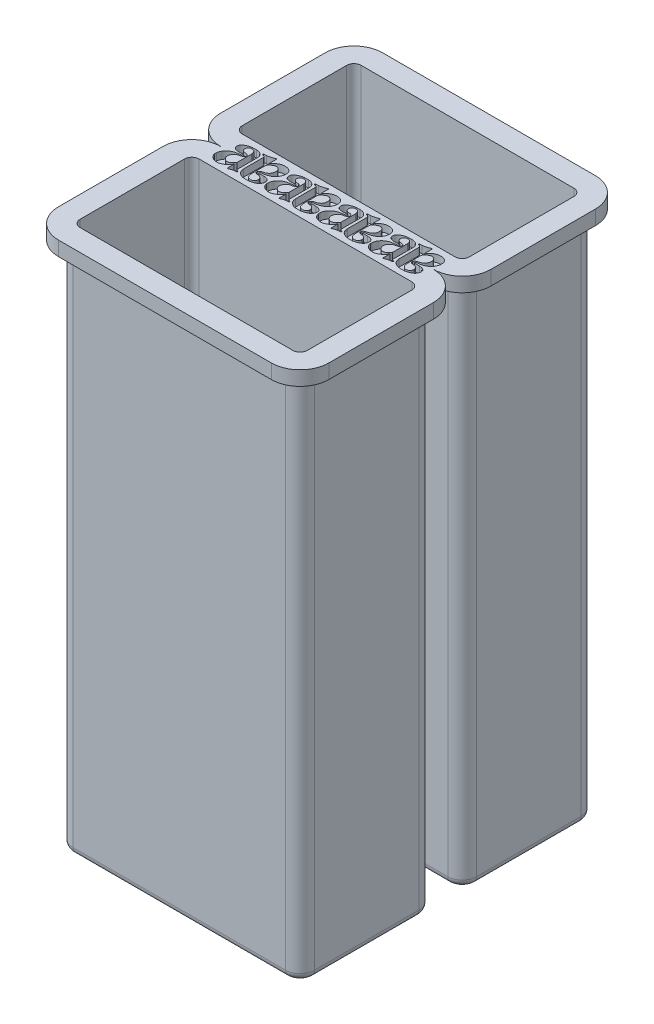
SolidWorks part; units mm, degrees
ref_plane "Alzado" through (0, 0, 0) normal (0, 0, 1) x (1, 0, 0)
ref_plane "Planta" through (0, 0, 0) normal (0, 1, 0) x (1, 0, 0)
ref_plane "Vista lateral" through (0, 0, 0) normal (1, 0, 0) x (0, 0, -1)
sketch "Croquis1" plane through (0, 0, 0) normal (0, 1, 0) x (1, 0, 0)
  line L0 (14.765, 0) -> (-14.765, 0) construction
  line L1 (-14.765, -3) -> (14.765, -3)
  line L2 (-14.765, 19.5) -> (14.765, 19.5)
  line L3 (-15.765, 18.5) -> (-15.765, 4)
  line L4 (-14.765, 3) -> (14.765, 3)
  line L5 (15.765, 18.5) -> (15.765, 4)
  line L6 (15.765, -18.5) -> (15.765, -4)
  line L7 (-14.765, -19.5) -> (14.765, -19.5)
  line L8 (-15.765, -18.5) -> (-15.765, -4)
  line L9 (-18.765, 18.5) -> (-18.765, 4)
  line L11 (18.765, 18.5) -> (18.765, 4)
  line L12 (-14.765, 22.5) -> (14.765, 22.5)
  line L13 (-14.765, 0) -> (14.765, 0) construction
  line L14 (18.765, -18.5) -> (18.765, -4)
  line L15 (-14.765, -22.5) -> (14.765, -22.5)
  line L16 (-18.765, -18.5) -> (-18.765, -4)
  line L17 (0, 0) -> (0, -22.5) construction
  arc A0 (-15.765, 4) -> (-14.765, 3) centre (-14.765, 4) ccw
  arc A1 (14.765, 3) -> (15.765, 4) centre (14.765, 4) ccw
  arc A2 (14.765, 19.5) -> (15.765, 18.5) centre (14.765, 18.5) cw
  arc A3 (-14.765, 19.5) -> (-15.765, 18.5) centre (-14.765, 18.5) ccw
  arc A4 (14.765, -3) -> (15.765, -4) centre (14.765, -4) cw
  arc A5 (14.765, -19.5) -> (15.765, -18.5) centre (14.765, -18.5) ccw
  arc A6 (-15.765, -4) -> (-14.765, -3) centre (-14.765, -4) cw
  arc A7 (-14.765, -19.5) -> (-15.765, -18.5) centre (-14.765, -18.5) cw
  arc A10 (14.765, 22.5) -> (18.765, 18.5) centre (14.765, 18.5) cw
  arc A11 (-14.765, 22.5) -> (-18.765, 18.5) centre (-14.765, 18.5) ccw
  arc A12 (14.765, 0) -> (18.765, 4) centre (14.765, 4) ccw construction
  arc A13 (-18.765, 4) -> (-14.765, 0) centre (-14.765, 4) ccw construction
  arc A14 (14.765, -22.5) -> (18.765, -18.5) centre (14.765, -18.5) ccw
  arc A15 (-14.765, -22.5) -> (-18.765, -18.5) centre (-14.765, -18.5) cw
  arc A16 (-14.765, 0) -> (-18.765, -4) centre (-14.765, -4) ccw
  arc A17 (14.765, 0) -> (18.765, -4) centre (14.765, -4) cw
  arc A18 (14.765, 0) -> (18.765, 4) centre (14.765, 4) ccw
  arc A19 (-14.765, 0) -> (-18.765, 4) centre (-14.765, 4) cw
  point P4 (0, 0)
  point P10 (0, 19.5)
  point P15 (15.765, 3)
  point P18 (15.765, 19.5)
  point P21 (-15.765, 19.5)
  dimension "D4" = 1
  dimension "D1" = 31.53
  dimension "D2" = 16.5
  dimension "D3" = 6
  dimension "D5" = 3
extrude "Saliente-Extruir1" add sketch "Croquis1" against normal blind 74
sketch "Croquis2" plane through (0, -74, 0) normal (0, -1, 0) x (1, 0, 0)
  line L0 (-14.765, 2) -> (14.765, 2)
  line L1 (14.765, -20.5) -> (-14.765, -20.5)
  line L2 (16.765, -4) -> (16.765, -18.5)
  line L3 (-14.765, -2) -> (14.765, -2)
  line L4 (-16.765, -18.5) -> (-16.765, -4)
  line L6 (-20, 23.5) -> (20, 23.5)
  line L7 (-20, 23.5) -> (-20, -23.5)
  line L8 (-20, -23.5) -> (20, -23.5)
  line L9 (20, 23.5) -> (20, -23.5)
  line L10 (-20, 23.5) -> (20, -23.5) construction
  line L11 (-20, -23.5) -> (20, 23.5) construction
  line L16 (14.765, 0) -> (-14.765, 0) construction
  line L19 (16.765, 4) -> (16.765, 18.5)
  line L20 (14.765, 20.5) -> (-14.765, 20.5)
  line L21 (-16.765, 18.5) -> (-16.765, 4)
  line L22 (16.765, 4) -> (16.765, 18.5)
  line L23 (14.765, 20.5) -> (-14.765, 20.5)
  line L24 (-16.765, 18.5) -> (-16.765, 4)
  arc A0 (16.765, -18.5) -> (14.765, -20.5) centre (14.765, -18.5) cw
  arc A1 (14.765, -2) -> (16.765, -4) centre (14.765, -4) cw
  arc A2 (-16.765, -4) -> (-14.765, -2) centre (-14.765, -4) cw
  arc A3 (-14.765, -20.5) -> (-16.765, -18.5) centre (-14.765, -18.5) cw
  arc A21 (14.765, 2) -> (16.765, 4) centre (14.765, 4) ccw
  arc A22 (-16.765, 4) -> (-14.765, 2) centre (-14.765, 4) ccw
  arc A23 (16.765, 18.5) -> (14.765, 20.5) centre (14.765, 18.5) ccw
  arc A24 (-14.765, 20.5) -> (-16.765, 18.5) centre (-14.765, 18.5) ccw
  arc A25 (14.765, 2) -> (16.765, 4) centre (14.765, 4) ccw
  arc A26 (-16.765, 4) -> (-14.765, 2) centre (-14.765, 4) ccw
  arc A27 (16.765, 18.5) -> (14.765, 20.5) centre (14.765, 18.5) ccw
  arc A28 (-14.765, 20.5) -> (-16.765, 18.5) centre (-14.765, 18.5) ccw
  point P3 (0, 0)
  point P15 (0, 0)
  dimension "D2" = 40
  dimension "D3" = 47
  dimension "D1" = 1
extrude "Cortar-Extruir1" cut sketch "Croquis2" against normal blind 72
sketch "Croquis3" plane through (0, -74, 0) normal (0, -1, 0) x (1, 0, 0)
  line L4 (-14.765, 2) -> (14.765, 2)
  line L5 (16.765, 4) -> (16.765, 18.5)
  line L6 (14.765, 20.5) -> (-14.765, 20.5)
  line L7 (-16.765, 18.5) -> (-16.765, 4)
  line L8 (-14.765, 2) -> (14.765, 2)
  line L9 (16.765, 4) -> (16.765, 18.5)
  line L10 (14.765, 20.5) -> (-14.765, 20.5)
  line L11 (-16.765, 18.5) -> (-16.765, 4)
  line L12 (-14.765, -20.5) -> (14.765, -20.5)
  line L13 (16.765, -18.5) -> (16.765, -4)
  line L14 (14.765, -2) -> (-14.765, -2)
  line L15 (-16.765, -4) -> (-16.765, -18.5)
  line L16 (-14.765, -20.5) -> (14.765, -20.5)
  line L17 (16.765, -18.5) -> (16.765, -4)
  line L18 (14.765, -2) -> (-14.765, -2)
  line L19 (-16.765, -4) -> (-16.765, -18.5)
  arc A4 (14.765, 2) -> (16.765, 4) centre (14.765, 4) ccw
  arc A5 (16.765, 18.5) -> (14.765, 20.5) centre (14.765, 18.5) ccw
  arc A6 (-14.765, 20.5) -> (-16.765, 18.5) centre (-14.765, 18.5) ccw
  arc A7 (-16.765, 4) -> (-14.765, 2) centre (-14.765, 4) ccw
  arc A8 (14.765, 2) -> (16.765, 4) centre (14.765, 4) ccw
  arc A9 (16.765, 18.5) -> (14.765, 20.5) centre (14.765, 18.5) ccw
  arc A10 (-14.765, 20.5) -> (-16.765, 18.5) centre (-14.765, 18.5) ccw
  arc A11 (-16.765, 4) -> (-14.765, 2) centre (-14.765, 4) ccw
  arc A12 (14.765, -20.5) -> (16.765, -18.5) centre (14.765, -18.5) ccw
  arc A13 (16.765, -4) -> (14.765, -2) centre (14.765, -4) ccw
  arc A14 (-14.765, -2) -> (-16.765, -4) centre (-14.765, -4) ccw
  arc A15 (-16.765, -18.5) -> (-14.765, -20.5) centre (-14.765, -18.5) ccw
  arc A16 (14.765, -20.5) -> (16.765, -18.5) centre (14.765, -18.5) ccw
  arc A17 (16.765, -4) -> (14.765, -2) centre (14.765, -4) ccw
  arc A18 (-14.765, -2) -> (-16.765, -4) centre (-14.765, -4) ccw
  arc A19 (-16.765, -18.5) -> (-14.765, -20.5) centre (-14.765, -18.5) ccw
  dimension "D1" = 0
  dimension "D2" = 0
extrude "Saliente-Extruir2" add sketch "Croquis3" along normal blind 1
fillet "Redondeo1" radius 1 32 edges at (16.1792, -75, -19.9142) (0, -75, -20.5) (-16.1792, -75, -19.9142) (-16.765, -75, -11.25) (-16.1792, -75, -2.5858) (0, -75, -2) (16.1792, -75, -2.5858) (16.1792, -75, 2.5858) (0, -75, 2) (-16.1792, -75, 2.5858) (-16.765, -75, 11.25) (-16.1792, -75, 19.9142) (0, -75, 20.5) (16.1792, -75, 19.9142) (15.4721, -74, 19.2071) (0, -74, 19.5) (-15.4721, -74, 19.2071) (-15.765, -74, 11.25) (-15.4721, -74, 3.2929) (0, -74, 3) (15.4721, -74, 3.2929) (15.4721, -74, -3.2929) (0, -74, -3) (-15.4721, -74, -3.2929) (-15.765, -74, -11.25) (-15.4721, -74, -19.2071) (0, -74, -19.5) (15.4721, -74, -19.2071) (16.765, -75, -11.25) (16.765, -75, 11.25) (15.765, -74, 11.25) (15.765, -74, -11.25)
sketch "Croquis4" plane through (0, 0, 0) normal (0, 1, 0) x (1, 0, 0)
  line L0 (-11.8795, 2.0902) -> (-12.3883, 2.0791)
  line L1 (-14.2916, -1.0751) -> (-14.3008, -1.2959)
  line L2 (-10.8563, -1.6035) -> (-10.8563, 1.3159)
  line L3 (-11.7052, -1.1855) -> (-11.7052, -2.1001)
  line L4 (-10.5361, -1.872) -> (-10.5361, -1.8152)
  line L5 (-10.4779, -1.095) -> (-10.4779, 1.6439)
  line L6 (-11.7052, -0.7712) -> (-11.7052, 1.3159)
  line L7 (-9.33, -2.2034) -> (-8.6683, -2.2034)
  line L8 (-10.8563, 2.0647) -> (-10.4779, 2.0902)
  line L9 (-9.3463, 2.3214) -> (-9.3463, 1.297)
  line L10 (-6.9008, 1.297) -> (-6.9008, 1.03)
  line L11 (-7.3722, -1.2503) -> (-7.3722, -1.0751)
  line L12 (-8.1771, -0.5685) -> (-8.8775, -0.5685)
  line L13 (-9.3536, 0.8335) -> (-9.3536, -1.0859)
  line L14 (-8.1592, -1.4475) -> (-8.1592, -1.3614)
  line L15 (-8.7028, -0.8289) -> (-8.9661, -0.802)
  line L16 (-9.2161, -0.5685) -> (-9.2161, -0.4919)
  line L17 (-8.508, 1.4567) -> (-8.4165, 1.4567)
  line L18 (-3.3361, -1.872) -> (-3.3361, -1.8152)
  line L19 (-4.5052, -1.1855) -> (-4.5052, -2.1001)
  line L20 (-7.0916, -1.0751) -> (-7.1008, -1.2959)
  line L21 (-4.6795, 2.0902) -> (-5.1883, 2.0791)
  line L22 (-3.6563, -1.6035) -> (-3.6563, 1.3159)
  line L23 (-4.5052, -0.7712) -> (-4.5052, 1.3159)
  line L24 (0.2992, 1.297) -> (0.2992, 1.03)
  line L25 (-2.1463, 2.3214) -> (-2.1463, 1.297)
  line L26 (-3.6563, 2.0647) -> (-3.2779, 2.0902)
  line L27 (-3.2779, -1.095) -> (-3.2779, 1.6439)
  line L28 (-2.13, -2.2034) -> (-1.4683, -2.2034)
  line L29 (-0.1722, -1.2503) -> (-0.1722, -1.0751)
  line L30 (-0.9771, -0.5685) -> (-1.6775, -0.5685)
  line L31 (-1.308, 1.4567) -> (-1.2165, 1.4567)
  line L32 (-2.0161, -0.5685) -> (-2.0161, -0.4919)
  line L33 (-1.5028, -0.8289) -> (-1.7661, -0.802)
  line L34 (-0.9592, -1.4475) -> (-0.9592, -1.3614)
  line L35 (-2.1536, 0.8335) -> (-2.1536, -1.0859)
  line L36 (3.8639, -1.872) -> (3.8639, -1.8152)
  line L37 (2.6948, -1.1855) -> (2.6948, -2.1001)
  line L38 (0.1084, -1.0751) -> (0.0992, -1.2959)
  line L39 (2.5205, 2.0902) -> (2.0117, 2.0791)
  line L40 (3.5437, -1.6035) -> (3.5437, 1.3159)
  line L41 (2.6948, -0.7712) -> (2.6948, 1.3159)
  line L42 (7.4992, 1.297) -> (7.4992, 1.03)
  line L43 (5.0537, 2.3214) -> (5.0537, 1.297)
  line L44 (3.5437, 2.0647) -> (3.9221, 2.0902)
  line L45 (3.9221, -1.095) -> (3.9221, 1.6439)
  line L46 (5.07, -2.2034) -> (5.7317, -2.2034)
  line L47 (7.0278, -1.2503) -> (7.0278, -1.0751)
  line L48 (6.2229, -0.5685) -> (5.5225, -0.5685)
  line L49 (5.892, 1.4567) -> (5.9835, 1.4567)
  line L50 (5.1839, -0.5685) -> (5.1839, -0.4919)
  line L51 (5.6972, -0.8289) -> (5.4339, -0.802)
  line L52 (6.2408, -1.4475) -> (6.2408, -1.3614)
  line L53 (5.0464, 0.8335) -> (5.0464, -1.0859)
  line L54 (11.0639, -1.872) -> (11.0639, -1.8152)
  line L55 (9.8948, -1.1855) -> (9.8948, -2.1001)
  line L56 (7.3084, -1.0751) -> (7.2992, -1.2959)
  line L57 (9.7205, 2.0902) -> (9.2117, 2.0791)
  line L58 (10.7437, -1.6035) -> (10.7437, 1.3159)
  line L59 (9.8948, -0.7712) -> (9.8948, 1.3159)
  line L60 (14.6992, 1.297) -> (14.6992, 1.03)
  line L61 (12.2537, 2.3214) -> (12.2537, 1.297)
  line L62 (10.7437, 2.0647) -> (11.1221, 2.0902)
  line L63 (11.1221, -1.095) -> (11.1221, 1.6439)
  line L64 (12.27, -2.2034) -> (12.9317, -2.2034)
  line L65 (14.2278, -1.2503) -> (14.2278, -1.0751)
  line L66 (13.4229, -0.5685) -> (12.7225, -0.5685)
  line L67 (13.092, 1.4567) -> (13.1835, 1.4567)
  line L68 (12.3839, -0.5685) -> (12.3839, -0.4919)
  line L69 (12.8972, -0.8289) -> (12.6339, -0.802)
  line L70 (13.4408, -1.4475) -> (13.4408, -1.3614)
  line L71 (12.2464, 0.8335) -> (12.2464, -1.0859)
  arc A0 (-11.7052, -2.1001) -> (-11.6285, -2.1768) centre (-11.6285, -2.1001) ccw
  arc A1 (-11.6285, -2.1768) -> (-11.5541, -2.1543) centre (-11.6285, -2.0422) ccw
  arc A2 (-10.5845, -1.9202) -> (-10.5361, -1.872) centre (-10.5921, -1.8643) ccw
  arc A3 (-10.5361, -1.8152) -> (-10.5845, -1.7738) centre (-10.578, -1.8152) ccw
  arc A4 (-9.4632, 2.3843) -> (-9.3463, 2.3214) centre (-9.4267, 2.3121) cw
  arc A5 (-3.3361, -1.8152) -> (-3.3845, -1.7738) centre (-3.378, -1.8152) ccw
  arc A6 (-3.3845, -1.9202) -> (-3.3361, -1.872) centre (-3.3921, -1.8643) ccw
  arc A7 (-4.4285, -2.1768) -> (-4.3541, -2.1543) centre (-4.4285, -2.0422) ccw
  arc A8 (-4.5052, -2.1001) -> (-4.4285, -2.1768) centre (-4.4285, -2.1001) ccw
  arc A9 (-2.2632, 2.3843) -> (-2.1463, 2.3214) centre (-2.2267, 2.3121) cw
  arc A10 (3.8639, -1.8152) -> (3.8155, -1.7738) centre (3.822, -1.8152) ccw
  arc A11 (3.8155, -1.9202) -> (3.8639, -1.872) centre (3.8079, -1.8643) ccw
  arc A12 (2.7715, -2.1768) -> (2.8459, -2.1543) centre (2.7715, -2.0422) ccw
  arc A13 (2.6948, -2.1001) -> (2.7715, -2.1768) centre (2.7715, -2.1001) ccw
  arc A14 (4.9368, 2.3843) -> (5.0537, 2.3214) centre (4.9733, 2.3121) cw
  arc A15 (11.0639, -1.8152) -> (11.0155, -1.7738) centre (11.022, -1.8152) ccw
  arc A16 (11.0155, -1.9202) -> (11.0639, -1.872) centre (11.0079, -1.8643) ccw
  arc A17 (9.9715, -2.1768) -> (10.0459, -2.1543) centre (9.9715, -2.0422) ccw
  arc A18 (9.8948, -2.1001) -> (9.9715, -2.1768) centre (9.9715, -2.1001) ccw
  arc A19 (12.1368, 2.3843) -> (12.2537, 2.3214) centre (12.1733, 2.3121) cw
  spline S0 degree 3 poles (-11.8795, 2.0902) (-11.7974, 2.092) (-11.6305, 2.0703) (-11.3623, 1.9941) (-11.1105, 1.8336) (-10.9258, 1.5934) (-10.8563, 1.4113) (-10.8563, 1.3159) knots 0 0 0 0 0.176265 0.35706 0.595786 0.800277 1 1 1 1
  spline S1 degree 3 poles (-12.3883, 2.0791) (-12.7283, 2.0457) (-13.1841, 1.8972) (-13.7331, 1.4302) (-13.6772, 0.9392) (-13.4327, 0.71) (-13.3179, 0.6682) (-13.2223, 0.6559) knots 0 0 0 0 0.418754 0.587265 0.852531 0.886586 1 1 1 1
  spline S2 degree 3 poles (-13.2223, 0.6559) (-12.9982, 0.609) (-12.6973, 0.5949) (-12.3609, 0.644) (-12.2286, 0.6513) (-12.1431, 0.6472) (-12.0989, 0.6029) (-12.0922, 0.5409) (-12.1577, 0.4818) (-12.2694, 0.4336) (-12.4314, 0.4071) (-12.635, 0.3836) (-12.8585, 0.3316) (-13.1059, 0.2894) (-13.5865, 0.1158) (-14.0684, -0.2842) (-14.2698, -0.8112) (-14.2893, -1.0182) (-14.2916, -1.0751) knots 0 0 0 0 0.16467 0.215991 0.244355 0.261612 0.275207 0.285849 0.302822 0.332909 0.374904 0.420011 0.481325 0.540461 0.600937 0.850065 0.958911 1 1 1 1
  spline S3 degree 3 poles (-14.3008, -1.2959) (-14.2674, -1.4932) (-14.0737, -1.871) (-13.5431, -2.1245) (-12.6172, -2.1978) (-11.9671, -1.6463) (-11.7052, -1.1855) knots 0 0 0 0 0.180676 0.357503 0.502937 1 1 1 1
  spline S4 degree 3 poles (-11.5541, -2.1543) (-11.4032, -2.0871) (-11.1767, -1.9819) (-10.8429, -1.9427) (-10.674, -1.9324) (-10.5845, -1.9202) knots 0 0 0 0 0.497894 0.728418 1 1 1 1
  spline S5 degree 3 poles (-10.8563, -1.6035) (-10.8338, -1.6453) (-10.7638, -1.7382) (-10.6485, -1.7738) (-10.5845, -1.7738) knots 0 0 0 0 0.425938 1 1 1 1
  spline S6 degree 3 poles (-11.7052, 1.3159) (-11.7489, 1.4579) (-11.8095, 1.7213) (-12.1949, 1.9345) (-12.6581, 1.8476) (-12.8507, 1.4239) (-12.7274, 1.0605) (-12.4075, 0.9213) (-12.1377, 0.943) (-11.9308, 0.8629) (-11.7694, 0.691) (-11.8191, 0.4205) (-12.0046, 0.3299) (-12.1577, 0.2775) (-12.359, 0.2127) (-12.5837, 0.1872) (-12.8199, 0.0293) (-13.1073, -0.2583) (-13.2845, -0.943) (-12.4071, -1.6606) (-11.8474, -1.0104) (-11.7052, -0.7712) knots 0 0 0 0 0.066893 0.099947 0.178793 0.231586 0.277149 0.325593 0.366012 0.390455 0.416998 0.460092 0.480657 0.501538 0.528892 0.569983 0.594816 0.647098 0.741155 0.856429 1 1 1 1
  spline S7 degree 3 poles (-10.4779, -1.095) (-10.4569, -1.3671) (-10.3332, -1.7902) (-9.8145, -2.0753) (-9.5443, -2.1886) (-9.33, -2.2034) knots 0 0 0 0 0.490284 0.645382 1 1 1 1
  spline S8 degree 3 poles (-10.4779, 1.6439) (-10.471, 1.7292) (-10.558, 1.8321) (-10.7053, 1.8899) (-10.8033, 1.881) (-10.8927, 1.9298) (-10.9089, 2.0261) (-10.8563, 2.0647) knots 0 0 0 0 0.32969 0.569438 0.670985 0.756454 1 1 1 1
  spline S9 degree 3 poles (-10.4779, 2.0902) (-10.1218, 2.1242) (-9.7835, 2.2223) (-9.4632, 2.3843) knots 0 0 0 0 1 1 1 1
  spline S10 degree 3 poles (-9.3463, 1.297) (-9.1088, 1.6036) (-8.6549, 2.0049) (-7.6253, 2.1838) (-6.9328, 1.8962) (-6.9008, 1.297) knots 0 0 0 0 0.382899 0.543112 1 1 1 1
  spline S11 degree 3 poles (-8.6683, -2.2034) (-8.3325, -2.132) (-7.7399, -1.9922) (-7.392, -1.4705) (-7.3722, -1.2503) knots 0 0 0 0 0.615534 1 1 1 1
  spline S12 degree 3 poles (-7.3722, -1.0751) (-7.3842, -0.914) (-7.5517, -0.7085) (-7.8817, -0.5973) (-8.0793, -0.5685) (-8.1771, -0.5685) knots 0 0 0 0 0.437104 0.707414 1 1 1 1
  spline S13 degree 3 poles (-8.8775, -0.5685) (-8.9228, -0.5542) (-8.9401, -0.4697) (-8.8733, -0.4141) (-8.7908, -0.3761) (-8.6711, -0.3576) (-7.8566, -0.2497) (-7.0961, 0.0611) (-6.9008, 1.03) knots 0 0 0 0 0.049332 0.062709 0.093396 0.148478 0.19489 1 1 1 1
  spline S14 degree 3 poles (-9.3536, -1.0859) (-9.3421, -1.2915) (-9.2881, -1.752) (-8.5669, -2.0546) (-8.1741, -1.6939) (-8.1592, -1.4475) knots 0 0 0 0 0.334106 0.635983 1 1 1 1
  spline S15 degree 3 poles (-8.1592, -1.3614) (-8.1716, -1.2326) (-8.2492, -1.0383) (-8.4784, -0.8769) (-8.6229, -0.837) (-8.7028, -0.8289) knots 0 0 0 0 0.474595 0.703744 1 1 1 1
  spline S16 degree 3 poles (-8.9661, -0.802) (-9.0567, -0.8031) (-9.157, -0.725) (-9.2161, -0.6078) (-9.2161, -0.5685) knots 0 0 0 0 0.677295 1 1 1 1
  spline S17 degree 3 poles (-9.2161, -0.4919) (-9.1758, -0.3616) (-8.9899, -0.186) (-8.6397, -0.1356) (-8.3539, -0.0039) (-8.0703, 0.1979) (-7.9083, 0.5772) (-7.8935, 0.9452) (-8.0052, 1.2097) (-8.1291, 1.3467) (-8.2734, 1.4362) (-8.3814, 1.4567) (-8.4165, 1.4567) knots 0 0 0 0 0.139662 0.240587 0.3619 0.464508 0.59299 0.774775 0.829203 0.886762 0.964191 1 1 1 1
  spline S18 degree 3 poles (-9.3536, 0.8335) (-9.25, 1.0592) (-8.9786, 1.3049) (-8.6311, 1.4567) (-8.508, 1.4567) knots 0 0 0 0 0.663348 1 1 1 1
  spline S19 degree 3 poles (-3.6563, -1.6035) (-3.6338, -1.6453) (-3.5638, -1.7382) (-3.4485, -1.7738) (-3.3845, -1.7738) knots 0 0 0 0 0.425938 1 1 1 1
  spline S20 degree 3 poles (-4.3541, -2.1543) (-4.2032, -2.0871) (-3.9767, -1.9819) (-3.6429, -1.9427) (-3.474, -1.9324) (-3.3845, -1.9202) knots 0 0 0 0 0.497894 0.728418 1 1 1 1
  spline S21 degree 3 poles (-7.1008, -1.2959) (-7.0674, -1.4932) (-6.8737, -1.871) (-6.3431, -2.1245) (-5.4172, -2.1978) (-4.7671, -1.6463) (-4.5052, -1.1855) knots 0 0 0 0 0.180676 0.357503 0.502937 1 1 1 1
  spline S22 degree 3 poles (-6.0223, 0.6559) (-5.7982, 0.609) (-5.4973, 0.5949) (-5.1609, 0.644) (-5.0286, 0.6513) (-4.9431, 0.6472) (-4.8989, 0.6029) (-4.8922, 0.5409) (-4.9577, 0.4818) (-5.0694, 0.4336) (-5.2314, 0.4071) (-5.435, 0.3836) (-5.6585, 0.3316) (-5.9059, 0.2894) (-6.3865, 0.1158) (-6.8694, -0.2842) (-7.0687, -0.8113) (-7.0901, -1.0182) (-7.0916, -1.0751) knots 0 0 0 0 0.16467 0.215991 0.244355 0.261612 0.275207 0.285849 0.302822 0.332909 0.374904 0.420011 0.481325 0.540461 0.600937 0.850065 0.958911 1 1 1 1
  spline S23 degree 3 poles (-5.1883, 2.0791) (-5.5283, 2.0457) (-5.9841, 1.8972) (-6.5331, 1.4302) (-6.4772, 0.9392) (-6.2327, 0.71) (-6.1179, 0.6682) (-6.0223, 0.6559) knots 0 0 0 0 0.418754 0.587265 0.852531 0.886586 1 1 1 1
  spline S24 degree 3 poles (-4.6795, 2.0902) (-4.5974, 2.092) (-4.4305, 2.0703) (-4.1623, 1.9941) (-3.9105, 1.8336) (-3.7258, 1.5934) (-3.6563, 1.4113) (-3.6563, 1.3159) knots 0 0 0 0 0.176265 0.35706 0.595786 0.800277 1 1 1 1
  spline S25 degree 3 poles (-4.5052, 1.3159) (-4.5489, 1.4579) (-4.6095, 1.7213) (-4.9949, 1.9345) (-5.4581, 1.8476) (-5.6507, 1.4239) (-5.5274, 1.0605) (-5.2075, 0.9213) (-4.9377, 0.943) (-4.7308, 0.8629) (-4.5694, 0.691) (-4.6191, 0.4205) (-4.8046, 0.3299) (-4.9577, 0.2775) (-5.159, 0.2127) (-5.3837, 0.1872) (-5.6199, 0.0293) (-5.9073, -0.2583) (-6.0845, -0.943) (-5.2071, -1.6606) (-4.6474, -1.0104) (-4.5052, -0.7712) knots 0 0 0 0 0.066893 0.099947 0.178793 0.231586 0.277149 0.325593 0.366012 0.390455 0.416998 0.460092 0.480657 0.501538 0.528892 0.569983 0.594816 0.647098 0.741155 0.856429 1 1 1 1
  spline S26 degree 3 poles (-1.6775, -0.5685) (-1.7228, -0.5542) (-1.7401, -0.4697) (-1.6733, -0.4141) (-1.5908, -0.3761) (-1.4711, -0.3576) (-0.6566, -0.2497) (0.1039, 0.0611) (0.2992, 1.03) knots 0 0 0 0 0.049332 0.062709 0.093396 0.148478 0.19489 1 1 1 1
  spline S27 degree 3 poles (-2.1463, 1.297) (-1.9088, 1.6036) (-1.4549, 2.0049) (-0.4253, 2.1838) (0.2672, 1.8962) (0.2992, 1.297) knots 0 0 0 0 0.382899 0.543112 1 1 1 1
  spline S28 degree 3 poles (-3.2779, 2.0902) (-2.9218, 2.1242) (-2.5835, 2.2223) (-2.2632, 2.3843) knots 0 0 0 0 1 1 1 1
  spline S29 degree 3 poles (-3.2779, 1.6439) (-3.271, 1.7292) (-3.358, 1.8321) (-3.5053, 1.8899) (-3.6033, 1.881) (-3.6927, 1.9298) (-3.7089, 2.0261) (-3.6563, 2.0647) knots 0 0 0 0 0.32969 0.569438 0.670985 0.756454 1 1 1 1
  spline S30 degree 3 poles (-3.2779, -1.095) (-3.2569, -1.3671) (-3.1332, -1.7902) (-2.6145, -2.0753) (-2.3443, -2.1886) (-2.13, -2.2034) knots 0 0 0 0 0.490284 0.645382 1 1 1 1
  spline S31 degree 3 poles (-1.4683, -2.2034) (-1.1325, -2.132) (-0.5399, -1.9922) (-0.192, -1.4705) (-0.1722, -1.2503) knots 0 0 0 0 0.615534 1 1 1 1
  spline S32 degree 3 poles (-0.1722, -1.0751) (-0.1842, -0.914) (-0.3517, -0.7085) (-0.6817, -0.5973) (-0.8793, -0.5685) (-0.9771, -0.5685) knots 0 0 0 0 0.437104 0.707414 1 1 1 1
  spline S33 degree 3 poles (-2.1536, 0.8335) (-2.05, 1.0592) (-1.7786, 1.3049) (-1.4311, 1.4567) (-1.308, 1.4567) knots 0 0 0 0 0.663348 1 1 1 1
  spline S34 degree 3 poles (-2.0161, -0.4919) (-1.9758, -0.3616) (-1.7899, -0.186) (-1.4397, -0.1356) (-1.1539, -0.0039) (-0.8703, 0.1979) (-0.7083, 0.5772) (-0.6935, 0.9452) (-0.8052, 1.2097) (-0.9291, 1.3467) (-1.0734, 1.4362) (-1.1814, 1.4567) (-1.2165, 1.4567) knots 0 0 0 0 0.139662 0.240587 0.3619 0.464508 0.59299 0.774775 0.829203 0.886762 0.964191 1 1 1 1
  spline S35 degree 3 poles (-1.7661, -0.802) (-1.8567, -0.8031) (-1.957, -0.725) (-2.0161, -0.6078) (-2.0161, -0.5685) knots 0 0 0 0 0.677295 1 1 1 1
  spline S36 degree 3 poles (-0.9592, -1.3614) (-0.9716, -1.2326) (-1.0492, -1.0383) (-1.2784, -0.8769) (-1.4229, -0.837) (-1.5028, -0.8289) knots 0 0 0 0 0.474595 0.703744 1 1 1 1
  spline S37 degree 3 poles (-2.1536, -1.0859) (-2.1421, -1.2915) (-2.0881, -1.752) (-1.3669, -2.0546) (-0.9741, -1.6939) (-0.9592, -1.4475) knots 0 0 0 0 0.334106 0.635983 1 1 1 1
  spline S38 degree 3 poles (3.5437, -1.6035) (3.5662, -1.6453) (3.6362, -1.7382) (3.7515, -1.7738) (3.8155, -1.7738) knots 0 0 0 0 0.425938 1 1 1 1
  spline S39 degree 3 poles (2.8459, -2.1543) (2.9968, -2.0871) (3.2233, -1.9819) (3.5571, -1.9427) (3.726, -1.9324) (3.8155, -1.9202) knots 0 0 0 0 0.497894 0.728418 1 1 1 1
  spline S40 degree 3 poles (0.0992, -1.2959) (0.1326, -1.4932) (0.3263, -1.871) (0.8569, -2.1245) (1.7828, -2.1978) (2.4329, -1.6463) (2.6948, -1.1855) knots 0 0 0 0 0.180676 0.357503 0.502937 1 1 1 1
  spline S41 degree 3 poles (1.1777, 0.6559) (1.4018, 0.609) (1.7027, 0.5949) (2.0391, 0.644) (2.1714, 0.6513) (2.2569, 0.6472) (2.3011, 0.6029) (2.3078, 0.5409) (2.2423, 0.4818) (2.1306, 0.4336) (1.9686, 0.4071) (1.765, 0.3836) (1.5415, 0.3316) (1.2941, 0.2894) (0.8135, 0.1158) (0.3306, -0.2842) (0.1313, -0.8113) (0.1099, -1.0182) (0.1084, -1.0751) knots 0 0 0 0 0.16467 0.215991 0.244355 0.261612 0.275207 0.285849 0.302822 0.332909 0.374904 0.420011 0.481325 0.540461 0.600937 0.850065 0.958911 1 1 1 1
  spline S42 degree 3 poles (2.0117, 2.0791) (1.6717, 2.0457) (1.2159, 1.8972) (0.6669, 1.4302) (0.7228, 0.9392) (0.9673, 0.71) (1.0821, 0.6682) (1.1777, 0.6559) knots 0 0 0 0 0.418754 0.587265 0.852531 0.886586 1 1 1 1
  spline S43 degree 3 poles (2.5205, 2.0902) (2.6026, 2.092) (2.7695, 2.0703) (3.0377, 1.9941) (3.2895, 1.8336) (3.4742, 1.5934) (3.5437, 1.4113) (3.5437, 1.3159) knots 0 0 0 0 0.176265 0.35706 0.595786 0.800277 1 1 1 1
  spline S44 degree 3 poles (2.6948, 1.3159) (2.6511, 1.4579) (2.5905, 1.7213) (2.2051, 1.9345) (1.7419, 1.8476) (1.5493, 1.4239) (1.6726, 1.0605) (1.9925, 0.9213) (2.2623, 0.943) (2.4692, 0.8629) (2.6306, 0.691) (2.5809, 0.4205) (2.3954, 0.3299) (2.2423, 0.2775) (2.041, 0.2127) (1.8163, 0.1872) (1.5801, 0.0293) (1.2927, -0.2583) (1.1155, -0.943) (1.9929, -1.6606) (2.5526, -1.0104) (2.6948, -0.7712) knots 0 0 0 0 0.066893 0.099947 0.178793 0.231586 0.277149 0.325593 0.366012 0.390455 0.416998 0.460092 0.480657 0.501538 0.528892 0.569983 0.594816 0.647098 0.741155 0.856429 1 1 1 1
  spline S45 degree 3 poles (5.5225, -0.5685) (5.4772, -0.5542) (5.4599, -0.4697) (5.5267, -0.4141) (5.6092, -0.3761) (5.7289, -0.3576) (6.5434, -0.2497) (7.3039, 0.0611) (7.4992, 1.03) knots 0 0 0 0 0.049332 0.062709 0.093396 0.148478 0.19489 1 1 1 1
  spline S46 degree 3 poles (5.0537, 1.297) (5.2912, 1.6036) (5.7451, 2.0049) (6.7747, 2.1838) (7.4672, 1.8962) (7.4992, 1.297) knots 0 0 0 0 0.382899 0.543112 1 1 1 1
  spline S47 degree 3 poles (3.9221, 2.0902) (4.2782, 2.1242) (4.6165, 2.2223) (4.9368, 2.3843) knots 0 0 0 0 1 1 1 1
  spline S48 degree 3 poles (3.9221, 1.6439) (3.929, 1.7292) (3.842, 1.8321) (3.6947, 1.8899) (3.5967, 1.881) (3.5073, 1.9298) (3.4911, 2.0261) (3.5437, 2.0647) knots 0 0 0 0 0.32969 0.569438 0.670985 0.756454 1 1 1 1
  spline S49 degree 3 poles (3.9221, -1.095) (3.9431, -1.3671) (4.0668, -1.7902) (4.5855, -2.0753) (4.8557, -2.1886) (5.07, -2.2034) knots 0 0 0 0 0.490284 0.645382 1 1 1 1
  spline S50 degree 3 poles (5.7317, -2.2034) (6.0675, -2.132) (6.6601, -1.9922) (7.008, -1.4705) (7.0278, -1.2503) knots 0 0 0 0 0.615534 1 1 1 1
  spline S51 degree 3 poles (7.0278, -1.0751) (7.0158, -0.914) (6.8483, -0.7085) (6.5183, -0.5973) (6.3207, -0.5685) (6.2229, -0.5685) knots 0 0 0 0 0.437104 0.707414 1 1 1 1
  spline S52 degree 3 poles (5.0464, 0.8335) (5.15, 1.0592) (5.4214, 1.3049) (5.7689, 1.4567) (5.892, 1.4567) knots 0 0 0 0 0.663348 1 1 1 1
  spline S53 degree 3 poles (5.1839, -0.4919) (5.2242, -0.3616) (5.4101, -0.186) (5.7603, -0.1356) (6.0461, -0.0039) (6.3297, 0.1979) (6.4917, 0.5772) (6.5065, 0.9452) (6.3948, 1.2097) (6.2709, 1.3467) (6.1266, 1.4362) (6.0186, 1.4567) (5.9835, 1.4567) knots 0 0 0 0 0.139662 0.240587 0.3619 0.464508 0.59299 0.774775 0.829203 0.886762 0.964191 1 1 1 1
  spline S54 degree 3 poles (5.4339, -0.802) (5.3433, -0.8031) (5.243, -0.725) (5.1839, -0.6078) (5.1839, -0.5685) knots 0 0 0 0 0.677295 1 1 1 1
  spline S55 degree 3 poles (6.2408, -1.3614) (6.2284, -1.2326) (6.1508, -1.0383) (5.9216, -0.8769) (5.7771, -0.837) (5.6972, -0.8289) knots 0 0 0 0 0.474595 0.703744 1 1 1 1
  spline S56 degree 3 poles (5.0464, -1.0859) (5.0579, -1.2915) (5.1119, -1.752) (5.8331, -2.0546) (6.2259, -1.6939) (6.2408, -1.4475) knots 0 0 0 0 0.334106 0.635983 1 1 1 1
  spline S57 degree 3 poles (10.7437, -1.6035) (10.7662, -1.6453) (10.8362, -1.7382) (10.9515, -1.7738) (11.0155, -1.7738) knots 0 0 0 0 0.425938 1 1 1 1
  spline S58 degree 3 poles (10.0459, -2.1543) (10.1968, -2.0871) (10.4233, -1.9819) (10.7571, -1.9427) (10.926, -1.9324) (11.0155, -1.9202) knots 0 0 0 0 0.497894 0.728418 1 1 1 1
  spline S59 degree 3 poles (7.2992, -1.2959) (7.3326, -1.4932) (7.5263, -1.871) (8.0569, -2.1245) (8.9828, -2.1978) (9.6329, -1.6463) (9.8948, -1.1855) knots 0 0 0 0 0.180676 0.357503 0.502937 1 1 1 1
  spline S60 degree 3 poles (8.3777, 0.6559) (8.6018, 0.609) (8.9027, 0.5949) (9.2391, 0.644) (9.3714, 0.6513) (9.4569, 0.6472) (9.5011, 0.6029) (9.5078, 0.5409) (9.4423, 0.4818) (9.3306, 0.4336) (9.1686, 0.4071) (8.965, 0.3836) (8.7415, 0.3316) (8.4941, 0.2894) (8.0135, 0.1158) (7.5306, -0.2842) (7.3313, -0.8113) (7.3099, -1.0182) (7.3084, -1.0751) knots 0 0 0 0 0.16467 0.215991 0.244355 0.261612 0.275207 0.285849 0.302822 0.332909 0.374904 0.420011 0.481325 0.540461 0.600937 0.850065 0.958911 1 1 1 1
  spline S61 degree 3 poles (9.2117, 2.0791) (8.8717, 2.0457) (8.4159, 1.8972) (7.8669, 1.4302) (7.9228, 0.9392) (8.1673, 0.71) (8.2821, 0.6682) (8.3777, 0.6559) knots 0 0 0 0 0.418754 0.587265 0.852531 0.886586 1 1 1 1
  spline S62 degree 3 poles (9.7205, 2.0902) (9.8026, 2.092) (9.9695, 2.0703) (10.2377, 1.9941) (10.4895, 1.8336) (10.6742, 1.5934) (10.7437, 1.4113) (10.7437, 1.3159) knots 0 0 0 0 0.176265 0.35706 0.595786 0.800277 1 1 1 1
  spline S63 degree 3 poles (9.8948, 1.3159) (9.8511, 1.4579) (9.7905, 1.7213) (9.4051, 1.9345) (8.9419, 1.8476) (8.7493, 1.4239) (8.8726, 1.0605) (9.1925, 0.9213) (9.4623, 0.943) (9.6692, 0.8629) (9.8306, 0.691) (9.7809, 0.4205) (9.5954, 0.3299) (9.4423, 0.2775) (9.241, 0.2127) (9.0163, 0.1872) (8.7801, 0.0293) (8.4927, -0.2583) (8.3155, -0.943) (9.1929, -1.6606) (9.7526, -1.0104) (9.8948, -0.7712) knots 0 0 0 0 0.066893 0.099947 0.178793 0.231586 0.277149 0.325593 0.366012 0.390455 0.416998 0.460092 0.480657 0.501538 0.528892 0.569983 0.594816 0.647098 0.741155 0.856429 1 1 1 1
  spline S64 degree 3 poles (12.7225, -0.5685) (12.6772, -0.5542) (12.6599, -0.4697) (12.7267, -0.4141) (12.8092, -0.3761) (12.9289, -0.3576) (13.7434, -0.2497) (14.5039, 0.0611) (14.6992, 1.03) knots 0 0 0 0 0.049332 0.062709 0.093396 0.148478 0.19489 1 1 1 1
  spline S65 degree 3 poles (12.2537, 1.297) (12.4912, 1.6036) (12.9451, 2.0049) (13.9747, 2.1838) (14.6672, 1.8962) (14.6992, 1.297) knots 0 0 0 0 0.382899 0.543112 1 1 1 1
  spline S66 degree 3 poles (11.1221, 2.0902) (11.4782, 2.1242) (11.8165, 2.2223) (12.1368, 2.3843) knots 0 0 0 0 1 1 1 1
  spline S67 degree 3 poles (11.1221, 1.6439) (11.129, 1.7292) (11.042, 1.8321) (10.8947, 1.8899) (10.7967, 1.881) (10.7073, 1.9298) (10.6911, 2.0261) (10.7437, 2.0647) knots 0 0 0 0 0.32969 0.569438 0.670985 0.756454 1 1 1 1
  spline S68 degree 3 poles (11.1221, -1.095) (11.1431, -1.3671) (11.2668, -1.7902) (11.7855, -2.0753) (12.0557, -2.1886) (12.27, -2.2034) knots 0 0 0 0 0.490284 0.645382 1 1 1 1
  spline S69 degree 3 poles (12.9317, -2.2034) (13.2675, -2.132) (13.8601, -1.9922) (14.208, -1.4705) (14.2278, -1.2503) knots 0 0 0 0 0.615534 1 1 1 1
  spline S70 degree 3 poles (14.2278, -1.0751) (14.2158, -0.914) (14.0483, -0.7085) (13.7183, -0.5973) (13.5207, -0.5685) (13.4229, -0.5685) knots 0 0 0 0 0.437104 0.707414 1 1 1 1
  spline S71 degree 3 poles (12.2464, 0.8335) (12.35, 1.0592) (12.6214, 1.3049) (12.9689, 1.4567) (13.092, 1.4567) knots 0 0 0 0 0.663348 1 1 1 1
  spline S72 degree 3 poles (12.3839, -0.4919) (12.4242, -0.3616) (12.6101, -0.186) (12.9603, -0.1356) (13.2461, -0.0039) (13.5297, 0.1979) (13.6917, 0.5772) (13.7065, 0.9452) (13.5948, 1.2097) (13.4709, 1.3467) (13.3266, 1.4362) (13.2186, 1.4567) (13.1835, 1.4567) knots 0 0 0 0 0.139662 0.240587 0.3619 0.464508 0.59299 0.774775 0.829203 0.886762 0.964191 1 1 1 1
  spline S73 degree 3 poles (12.6339, -0.802) (12.5433, -0.8031) (12.443, -0.725) (12.3839, -0.6078) (12.3839, -0.5685) knots 0 0 0 0 0.677295 1 1 1 1
  spline S74 degree 3 poles (13.4408, -1.3614) (13.4284, -1.2326) (13.3508, -1.0383) (13.1216, -0.8769) (12.9771, -0.837) (12.8972, -0.8289) knots 0 0 0 0 0.474595 0.703744 1 1 1 1
  spline S75 degree 3 poles (12.2464, -1.0859) (12.2579, -1.2915) (12.3119, -1.752) (13.0331, -2.0546) (13.4259, -1.6939) (13.4408, -1.4475) knots 0 0 0 0 0.334106 0.635983 1 1 1 1
split line "Línea de partición1"
sketch "Croquis5" plane through (0, 0, 0) normal (0, 1, 0) x (1, 0, 0)
  line L0 (11.1221, 1.6439) -> (11.1221, -1.095) construction
  line L1 (12.27, -2.2034) -> (12.9317, -2.2034) construction
  line L2 (14.2278, -1.2503) -> (14.2278, -1.0751) construction
  line L3 (13.4229, -0.5685) -> (12.7225, -0.5685) construction
  line L4 (14.6992, 1.03) -> (14.6992, 1.297) construction
  line L5 (12.2537, 1.297) -> (12.2537, 2.3214) construction
  line L6 (11.1221, 2.0902) -> (10.7437, 2.0647) construction
  line L7 (10.7437, -1.6035) -> (10.7437, 1.3159) construction
  line L8 (9.7205, 2.0902) -> (9.2117, 2.0791) construction
  line L9 (7.3084, -1.0751) -> (7.2992, -1.2959) construction
  line L10 (9.8948, -1.1855) -> (9.8948, -2.1001) construction
  line L11 (11.0639, -1.872) -> (11.0639, -1.8152) construction
  line L12 (3.9221, 1.6439) -> (3.9221, -1.095) construction
  line L13 (5.07, -2.2034) -> (5.7317, -2.2034) construction
  line L14 (7.0278, -1.2503) -> (7.0278, -1.0751) construction
  line L15 (6.2229, -0.5685) -> (5.5225, -0.5685) construction
  line L16 (7.4992, 1.03) -> (7.4992, 1.297) construction
  line L17 (5.0537, 1.297) -> (5.0537, 2.3214) construction
  line L18 (3.9221, 2.0902) -> (3.5437, 2.0647) construction
  line L19 (3.5437, -1.6035) -> (3.5437, 1.3159) construction
  line L20 (2.5205, 2.0902) -> (2.0117, 2.0791) construction
  line L21 (0.1084, -1.0751) -> (0.0992, -1.2959) construction
  line L22 (2.6948, -1.1855) -> (2.6948, -2.1001) construction
  line L23 (3.8639, -1.872) -> (3.8639, -1.8152) construction
  line L24 (-3.2779, 1.6439) -> (-3.2779, -1.095) construction
  line L25 (-2.13, -2.2034) -> (-1.4683, -2.2034) construction
  line L26 (-0.1722, -1.2503) -> (-0.1722, -1.0751) construction
  line L27 (-0.9771, -0.5685) -> (-1.6775, -0.5685) construction
  line L28 (0.2992, 1.03) -> (0.2992, 1.297) construction
  line L29 (-2.1463, 1.297) -> (-2.1463, 2.3214) construction
  line L30 (-3.2779, 2.0902) -> (-3.6563, 2.0647) construction
  line L31 (-3.6563, -1.6035) -> (-3.6563, 1.3159) construction
  line L32 (-4.6795, 2.0902) -> (-5.1883, 2.0791) construction
  line L33 (-7.0916, -1.0751) -> (-7.1008, -1.2959) construction
  line L34 (-4.5052, -1.1855) -> (-4.5052, -2.1001) construction
  line L35 (-3.3361, -1.872) -> (-3.3361, -1.8152) construction
  line L36 (-10.4779, 1.6439) -> (-10.4779, -1.095) construction
  line L37 (-9.33, -2.2034) -> (-8.6683, -2.2034) construction
  line L38 (-7.3722, -1.2503) -> (-7.3722, -1.0751) construction
  line L39 (-8.1771, -0.5685) -> (-8.8775, -0.5685) construction
  line L40 (-6.9008, 1.03) -> (-6.9008, 1.297) construction
  line L41 (-9.3463, 1.297) -> (-9.3463, 2.3214) construction
  line L42 (-10.4779, 2.0902) -> (-10.8563, 2.0647) construction
  line L43 (-10.8563, -1.6035) -> (-10.8563, 1.3159) construction
  line L44 (-11.8795, 2.0902) -> (-12.3883, 2.0791) construction
  line L45 (-14.2916, -1.0751) -> (-14.3008, -1.2959) construction
  line L46 (-11.7052, -1.1855) -> (-11.7052, -2.1001) construction
  line L47 (-10.5361, -1.872) -> (-10.5361, -1.8152) construction
  line L48 (11.1221, 1.6439) -> (11.1221, -1.095)
  line L49 (12.27, -2.2034) -> (12.9317, -2.2034)
  line L50 (14.2278, -1.2503) -> (14.2278, -1.0751)
  line L51 (13.4229, -0.5685) -> (12.7225, -0.5685)
  line L52 (14.6992, 1.03) -> (14.6992, 1.297)
  line L53 (12.2537, 1.297) -> (12.2537, 2.3214)
  line L54 (11.1221, 2.0902) -> (10.7437, 2.0647)
  line L55 (10.7437, -1.6035) -> (10.7437, 1.3159)
  line L56 (9.7205, 2.0902) -> (9.2117, 2.0791)
  line L57 (7.3084, -1.0751) -> (7.2992, -1.2959)
  line L58 (9.8948, -1.1855) -> (9.8948, -2.1001)
  line L59 (11.0639, -1.872) -> (11.0639, -1.8152)
  line L60 (3.9221, 1.6439) -> (3.9221, -1.095)
  line L61 (5.07, -2.2034) -> (5.7317, -2.2034)
  line L62 (7.0278, -1.2503) -> (7.0278, -1.0751)
  line L63 (6.2229, -0.5685) -> (5.5225, -0.5685)
  line L64 (7.4992, 1.03) -> (7.4992, 1.297)
  line L65 (5.0537, 1.297) -> (5.0537, 2.3214)
  line L66 (3.9221, 2.0902) -> (3.5437, 2.0647)
  line L67 (3.5437, -1.6035) -> (3.5437, 1.3159)
  line L68 (2.5205, 2.0902) -> (2.0117, 2.0791)
  line L69 (0.1084, -1.0751) -> (0.0992, -1.2959)
  line L70 (2.6948, -1.1855) -> (2.6948, -2.1001)
  line L71 (3.8639, -1.872) -> (3.8639, -1.8152)
  line L72 (-3.2779, 1.6439) -> (-3.2779, -1.095)
  line L73 (-2.13, -2.2034) -> (-1.4683, -2.2034)
  line L74 (-0.1722, -1.2503) -> (-0.1722, -1.0751)
  line L75 (-0.9771, -0.5685) -> (-1.6775, -0.5685)
  line L76 (0.2992, 1.03) -> (0.2992, 1.297)
  line L77 (-2.1463, 1.297) -> (-2.1463, 2.3214)
  line L78 (-3.2779, 2.0902) -> (-3.6563, 2.0647)
  line L79 (-3.6563, -1.6035) -> (-3.6563, 1.3159)
  line L80 (-4.6795, 2.0902) -> (-5.1883, 2.0791)
  line L81 (-7.0916, -1.0751) -> (-7.1008, -1.2959)
  line L82 (-4.5052, -1.1855) -> (-4.5052, -2.1001)
  line L83 (-3.3361, -1.872) -> (-3.3361, -1.8152)
  line L84 (-10.4779, 1.6439) -> (-10.4779, -1.095)
  line L85 (-9.33, -2.2034) -> (-8.6683, -2.2034)
  line L86 (-7.3722, -1.2503) -> (-7.3722, -1.0751)
  line L87 (-8.1771, -0.5685) -> (-8.8775, -0.5685)
  line L88 (-6.9008, 1.03) -> (-6.9008, 1.297)
  line L89 (-9.3463, 1.297) -> (-9.3463, 2.3214)
  line L90 (-10.4779, 2.0902) -> (-10.8563, 2.0647)
  line L91 (-10.8563, -1.6035) -> (-10.8563, 1.3159)
  line L92 (-11.8795, 2.0902) -> (-12.3883, 2.0791)
  line L93 (-14.2916, -1.0751) -> (-14.3008, -1.2959)
  line L94 (-11.7052, -1.1855) -> (-11.7052, -2.1001)
  line L95 (-10.5361, -1.872) -> (-10.5361, -1.8152)
  line L96 (13.4408, -1.4475) -> (13.4408, -1.3614) construction
  line L97 (12.8972, -0.8289) -> (12.6339, -0.802) construction
  line L98 (12.2464, 0.8335) -> (12.2464, -1.0859) construction
  line L99 (13.1835, 1.4567) -> (13.092, 1.4567) construction
  line L100 (12.3839, -0.5685) -> (12.3839, -0.4919) construction
  line L101 (9.8948, -0.7712) -> (9.8948, 1.3159) construction
  line L102 (6.2408, -1.4475) -> (6.2408, -1.3614) construction
  line L103 (5.6972, -0.8289) -> (5.4339, -0.802) construction
  line L104 (5.1839, -0.5685) -> (5.1839, -0.4919) construction
  line L105 (5.9835, 1.4567) -> (5.892, 1.4567) construction
  line L106 (5.0464, 0.8335) -> (5.0464, -1.0859) construction
  line L107 (2.6948, -0.7712) -> (2.6948, 1.3159) construction
  line L108 (-2.0161, -0.5685) -> (-2.0161, -0.4919) construction
  line L109 (-1.2165, 1.4567) -> (-1.308, 1.4567) construction
  line L110 (-0.9592, -1.4475) -> (-0.9592, -1.3614) construction
  line L111 (-1.5028, -0.8289) -> (-1.7661, -0.802) construction
  line L112 (-2.1536, 0.8335) -> (-2.1536, -1.0859) construction
  line L113 (-4.5052, -0.7712) -> (-4.5052, 1.3159) construction
  line L114 (-8.1592, -1.4475) -> (-8.1592, -1.3614) construction
  line L115 (-8.7028, -0.8289) -> (-8.9661, -0.802) construction
  line L116 (-9.2161, -0.5685) -> (-9.2161, -0.4919) construction
  line L117 (-8.4165, 1.4567) -> (-8.508, 1.4567) construction
  line L118 (-9.3536, 0.8335) -> (-9.3536, -1.0859) construction
  line L119 (-11.7052, -0.7712) -> (-11.7052, 1.3159) construction
  line L120 (13.4408, -1.4475) -> (13.4408, -1.3614)
  line L121 (12.8972, -0.8289) -> (12.6339, -0.802)
  line L122 (12.2464, 0.8335) -> (12.2464, -1.0859)
  line L123 (13.1835, 1.4567) -> (13.092, 1.4567)
  line L124 (12.3839, -0.5685) -> (12.3839, -0.4919)
  line L125 (9.8948, -0.7712) -> (9.8948, 1.3159)
  line L126 (6.2408, -1.4475) -> (6.2408, -1.3614)
  line L127 (5.6972, -0.8289) -> (5.4339, -0.802)
  line L128 (5.1839, -0.5685) -> (5.1839, -0.4919)
  line L129 (5.9835, 1.4567) -> (5.892, 1.4567)
  line L130 (5.0464, 0.8335) -> (5.0464, -1.0859)
  line L131 (2.6948, -0.7712) -> (2.6948, 1.3159)
  line L132 (-2.0161, -0.5685) -> (-2.0161, -0.4919)
  line L133 (-1.2165, 1.4567) -> (-1.308, 1.4567)
  line L134 (-0.9592, -1.4475) -> (-0.9592, -1.3614)
  line L135 (-1.5028, -0.8289) -> (-1.7661, -0.802)
  line L136 (-2.1536, 0.8335) -> (-2.1536, -1.0859)
  line L137 (-4.5052, -0.7712) -> (-4.5052, 1.3159)
  line L138 (-8.1592, -1.4475) -> (-8.1592, -1.3614)
  line L139 (-8.7028, -0.8289) -> (-8.9661, -0.802)
  line L140 (-9.2161, -0.5685) -> (-9.2161, -0.4919)
  line L141 (-8.4165, 1.4567) -> (-8.508, 1.4567)
  line L142 (-9.3536, 0.8335) -> (-9.3536, -1.0859)
  line L143 (-11.7052, -0.7712) -> (-11.7052, 1.3159)
  arc A0 (12.2537, 2.3214) -> (12.1368, 2.3843) centre (12.1733, 2.3121) ccw construction
  arc A1 (9.8948, -2.1001) -> (9.9715, -2.1768) centre (9.9715, -2.1001) ccw construction
  arc A2 (9.9715, -2.1768) -> (10.0459, -2.1543) centre (9.9715, -2.0422) ccw construction
  arc A3 (11.0155, -1.9202) -> (11.0639, -1.872) centre (11.0079, -1.8643) ccw construction
  arc A4 (11.0639, -1.8152) -> (11.0155, -1.7738) centre (11.022, -1.8152) ccw construction
  arc A5 (5.0537, 2.3214) -> (4.9368, 2.3843) centre (4.9733, 2.3121) ccw construction
  arc A6 (2.6948, -2.1001) -> (2.7715, -2.1768) centre (2.7715, -2.1001) ccw construction
  arc A7 (2.7715, -2.1768) -> (2.8459, -2.1543) centre (2.7715, -2.0422) ccw construction
  arc A8 (3.8155, -1.9202) -> (3.8639, -1.872) centre (3.8079, -1.8643) ccw construction
  arc A9 (3.8639, -1.8152) -> (3.8155, -1.7738) centre (3.822, -1.8152) ccw construction
  arc A10 (-2.1463, 2.3214) -> (-2.2632, 2.3843) centre (-2.2267, 2.3121) ccw construction
  arc A11 (-4.5052, -2.1001) -> (-4.4285, -2.1768) centre (-4.4285, -2.1001) ccw construction
  arc A12 (-4.4285, -2.1768) -> (-4.3541, -2.1543) centre (-4.4285, -2.0422) ccw construction
  arc A13 (-3.3845, -1.9202) -> (-3.3361, -1.872) centre (-3.3921, -1.8643) ccw construction
  arc A14 (-3.3361, -1.8152) -> (-3.3845, -1.7738) centre (-3.378, -1.8152) ccw construction
  arc A15 (-9.3463, 2.3214) -> (-9.4632, 2.3843) centre (-9.4267, 2.3121) ccw construction
  arc A16 (-11.7052, -2.1001) -> (-11.6285, -2.1768) centre (-11.6285, -2.1001) ccw construction
  arc A17 (-11.6285, -2.1768) -> (-11.5541, -2.1543) centre (-11.6285, -2.0422) ccw construction
  arc A18 (-10.5845, -1.9202) -> (-10.5361, -1.872) centre (-10.5921, -1.8643) ccw construction
  arc A19 (-10.5361, -1.8152) -> (-10.5845, -1.7738) centre (-10.578, -1.8152) ccw construction
  arc A20 (12.2537, 2.3214) -> (12.1368, 2.3843) centre (12.1733, 2.3121) ccw
  arc A21 (9.8948, -2.1001) -> (9.9715, -2.1768) centre (9.9715, -2.1001) ccw
  arc A22 (9.9715, -2.1768) -> (10.0459, -2.1543) centre (9.9715, -2.0422) ccw
  arc A23 (11.0155, -1.9202) -> (11.0639, -1.872) centre (11.0079, -1.8643) ccw
  arc A24 (11.0639, -1.8152) -> (11.0155, -1.7738) centre (11.022, -1.8152) ccw
  arc A25 (5.0537, 2.3214) -> (4.9368, 2.3843) centre (4.9733, 2.3121) ccw
  arc A26 (2.6948, -2.1001) -> (2.7715, -2.1768) centre (2.7715, -2.1001) ccw
  arc A27 (2.7715, -2.1768) -> (2.8459, -2.1543) centre (2.7715, -2.0422) ccw
  arc A28 (3.8155, -1.9202) -> (3.8639, -1.872) centre (3.8079, -1.8643) ccw
  arc A29 (3.8639, -1.8152) -> (3.8155, -1.7738) centre (3.822, -1.8152) ccw
  arc A30 (-2.1463, 2.3214) -> (-2.2632, 2.3843) centre (-2.2267, 2.3121) ccw
  arc A31 (-4.5052, -2.1001) -> (-4.4285, -2.1768) centre (-4.4285, -2.1001) ccw
  arc A32 (-4.4285, -2.1768) -> (-4.3541, -2.1543) centre (-4.4285, -2.0422) ccw
  arc A33 (-3.3845, -1.9202) -> (-3.3361, -1.872) centre (-3.3921, -1.8643) ccw
  arc A34 (-3.3361, -1.8152) -> (-3.3845, -1.7738) centre (-3.378, -1.8152) ccw
  arc A35 (-9.3463, 2.3214) -> (-9.4632, 2.3843) centre (-9.4267, 2.3121) ccw
  arc A36 (-11.7052, -2.1001) -> (-11.6285, -2.1768) centre (-11.6285, -2.1001) ccw
  arc A37 (-11.6285, -2.1768) -> (-11.5541, -2.1543) centre (-11.6285, -2.0422) ccw
  arc A38 (-10.5845, -1.9202) -> (-10.5361, -1.872) centre (-10.5921, -1.8643) ccw
  arc A39 (-10.5361, -1.8152) -> (-10.5845, -1.7738) centre (-10.578, -1.8152) ccw
  parabola Q0 (12.1368, 2.3843) -> (11.1221, 2.0902) construction
  parabola Q1 (4.9368, 2.3843) -> (3.9221, 2.0902) construction
  parabola Q2 (-2.2632, 2.3843) -> (-3.2779, 2.0902) construction
  parabola Q3 (-9.4632, 2.3843) -> (-10.4779, 2.0902) construction
  parabola Q4 (12.1368, 2.3843) -> (11.1221, 2.0902)
  parabola Q5 (4.9368, 2.3843) -> (3.9221, 2.0902)
  parabola Q6 (-2.2632, 2.3843) -> (-3.2779, 2.0902)
  parabola Q7 (-9.4632, 2.3843) -> (-10.4779, 2.0902)
  spline S0 degree 3 poles (-385.9743, -1961.0648) (64.3353, 77.4296) (5.7532, 1.2398) (17.6838, -5.3168) (26.9692, 8.6877) (893.0852, 1793.2614) knots -10.628718 -10.628718 -10.628718 -10.628718 0.490284 0.645382 12.370349 12.370349 12.370349 12.370349 only from (11.1221, -1.095) to (12.27, -2.2034) construction
  spline S1 degree 3 poles (1399.4902, -1443.5121) (-49.5211, 66.5173) (50.9666, -63.3164) (-5.7741, 52.2163) (-1856.8648, -706.088) knots -13.777234 -13.777234 -13.777234 -13.777234 0.615534 11.567989 11.567989 11.567989 11.567989 only from (12.9317, -2.2034) to (14.2278, -1.2503) construction
  spline S2 degree 3 poles (-1966.8861, 269.8246) (-1.8935, -51.2627) (18.3364, -2.1541) (8.1729, 1.2721) (-8.8523, -29.0382) (1577.561, -1246.5366) knots -12.995768 -12.995768 -12.995768 -12.995768 0.437104 0.707414 17.806109 17.806109 17.806109 17.806109 only from (14.2278, -1.0751) to (13.4229, -0.5685) construction
  spline S3 degree 3 poles (-65.1194, 1997.5207) (44.6731, -27.9578) (11.6544, -1.3057) (12.7267, -0.4141) (12.8092, -0.3761) (12.9289, -0.3576) (23.1181, 0.9914) (32.461, 39.1406) (-1373.0858, 1440.8026) knots -1.404534 -1.404534 -1.404534 -1.404534 0.049332 0.062709 0.093396 0.148478 0.19489 11.434684 11.434684 11.434684 11.434684 only from (12.7225, -0.5685) to (14.6992, 1.03) construction
  spline S4 degree 3 poles (-1828.8202, -772.7434) (36.0272, -49.7834) (20.7696, 3.3644) (3.1215, 0.298) (29.0064, -106.3678) (617.2117, 1907.1955) knots -6.599937 -6.599937 -6.599937 -6.599937 0.456888 0.617101 10.541785 10.541785 10.541785 10.541785 only from (14.6992, 1.297) to (12.2537, 1.297) construction
  spline S5 degree 3 poles (1077.0122, -1689.6791) (34.2782, 33.6833) (9.2319, 2.7356) (10.7967, 1.881) (10.8947, 1.8899) (13.5044, 0.8657) (-0.1627, -23.2541) (-1948.3285, -398.4349) knots -7.106971 -7.106971 -7.106971 -7.106971 0.243546 0.329015 0.430562 0.67031 12.222667 12.222667 12.222667 12.222667 only from (10.7437, 2.0647) to (11.1221, 1.6439) construction
  spline S6 degree 3 poles (-1985.0606, 129.1149) (-7.1935, -20.21) (13.1318, -1.6047) (10.4895, 1.8336) (10.2377, 1.9941) (4.866, 3.5191) (-7.0165, -20.6173) (502.5236, -1936.1307) knots -8.55762 -8.55762 -8.55762 -8.55762 0.199723 0.404214 0.64294 0.823735 12.335211 12.335211 12.335211 12.335211 only from (10.7437, 1.3159) to (9.7205, 2.0902) construction
  spline S7 degree 3 poles (-1809.8065, 830.2887) (109.7318, -151.6065) (20.0129, 11.7603) (7.8669, 1.4302) (7.9228, 0.9392) (12.2664, -3.1321) (79.2494, 85.0143) (-1880.6279, -654.4516) knots -18.006469 -18.006469 -18.006469 -18.006469 0.418754 0.587265 0.852531 0.886586 7.917637 7.917637 7.917637 7.917637 only from (9.2117, 2.0791) to (8.3777, 0.6559) construction
  spline S8 degree 3 poles (1706.329, 1052.6977) (-27.1344, 127.2617) (-4.983, -1.432) (9.2391, 0.644) (9.3714, 0.6513) (9.4569, 0.6472) (9.5011, 0.6029) (9.5078, 0.5409) (9.4423, 0.4818) (9.3306, 0.4336) (9.1686, 0.4071) (8.965, 0.3836) (8.7415, 0.3316) (8.4941, 0.2894) (8.0135, 0.1158) (0.3306, -6.247) (72.2991, -56.9211) (1506.0435, 1321.4766) knots -10.08665 -10.08665 -10.08665 -10.08665 0.16467 0.215991 0.244355 0.261612 0.275207 0.285849 0.302822 0.332909 0.374904 0.420011 0.481325 0.540461 0.600937 0.850065 7.197512 7.197512 7.197512 7.197512 only from (8.3777, 0.6559) to (7.3084, -1.0751) construction
  spline S9 degree 3 poles (953.0586, -1762.4613) (56.2881, 71.6442) (0.9545, 1.2693) (8.0569, -2.1245) (18.6138, -2.9602) (13.4942, 120.1288) (-1173.9747, -1612.2372) knots -6.229179 -6.229179 -6.229179 -6.229179 0.180676 0.357503 0.502937 9.522252 9.522252 9.522252 9.522252 only from (7.2992, -1.2959) to (9.8948, -1.1855) construction
  spline S10 degree 3 poles (-177.7686, 1988.9759) (9.2792, -55.2492) (0.123, 42.2366) (29.7099, -38.5573) (-450.5166, 1943.9643) knots -18.213584 -18.213584 -18.213584 -18.213584 0.497894 16.92396 16.92396 16.92396 16.92396 only from (10.0459, -2.1543) to (11.0155, -1.9202) construction
  spline S11 degree 3 poles (-1962.9116, 317.8097) (52.7151, 40.9835) (-24.1633, -46.2858) (39.4875, 44.4731) (-136.0942, -1996.0765) knots -27.947041 -27.947041 -27.947041 -27.947041 0.574062 27.797228 27.797228 27.797228 27.797228 only from (11.0155, -1.7738) to (10.7437, -1.6035) construction
  spline S12 degree 3 poles (-393.1743, -1961.0648) (57.1353, 77.4296) (-1.4468, 1.2398) (10.4838, -5.3168) (19.7692, 8.6877) (885.8852, 1793.2614) knots -10.628718 -10.628718 -10.628718 -10.628718 0.490284 0.645382 12.370349 12.370349 12.370349 12.370349 only from (3.9221, -1.095) to (5.07, -2.2034) construction
  spline S13 degree 3 poles (1392.2902, -1443.5121) (-56.7211, 66.5173) (43.7666, -63.3164) (-12.9741, 52.2163) (-1864.0648, -706.088) knots -13.777234 -13.777234 -13.777234 -13.777234 0.615534 11.567989 11.567989 11.567989 11.567989 only from (5.7317, -2.2034) to (7.0278, -1.2503) construction
  spline S14 degree 3 poles (-1974.0861, 269.8246) (-9.0935, -51.2627) (11.1364, -2.1541) (0.9729, 1.2721) (-16.0523, -29.0382) (1570.361, -1246.5366) knots -12.995768 -12.995768 -12.995768 -12.995768 0.437104 0.707414 17.806109 17.806109 17.806109 17.806109 only from (7.0278, -1.0751) to (6.2229, -0.5685) construction
  spline S15 degree 3 poles (-72.3194, 1997.5207) (37.4731, -27.9578) (4.4544, -1.3057) (5.5267, -0.4141) (5.6092, -0.3761) (5.7289, -0.3576) (15.9181, 0.9914) (25.261, 39.1406) (-1380.2858, 1440.8026) knots -1.404534 -1.404534 -1.404534 -1.404534 0.049332 0.062709 0.093396 0.148478 0.19489 11.434684 11.434684 11.434684 11.434684 only from (5.5225, -0.5685) to (7.4992, 1.03) construction
  spline S16 degree 3 poles (-1836.0202, -772.7434) (28.8272, -49.7834) (13.5696, 3.3644) (-4.0785, 0.298) (21.8064, -106.3678) (610.0117, 1907.1955) knots -6.599937 -6.599937 -6.599937 -6.599937 0.456888 0.617101 10.541785 10.541785 10.541785 10.541785 only from (7.4992, 1.297) to (5.0537, 1.297) construction
  spline S17 degree 3 poles (1069.8122, -1689.6791) (27.0782, 33.6833) (2.0319, 2.7356) (3.5967, 1.881) (3.6947, 1.8899) (6.3044, 0.8657) (-7.3627, -23.2541) (-1955.5285, -398.4349) knots -7.106971 -7.106971 -7.106971 -7.106971 0.243546 0.329015 0.430562 0.67031 12.222667 12.222667 12.222667 12.222667 only from (3.5437, 2.0647) to (3.9221, 1.6439) construction
  spline S18 degree 3 poles (-1992.2606, 129.1149) (-14.3935, -20.21) (5.9318, -1.6047) (3.2895, 1.8336) (3.0377, 1.9941) (-2.334, 3.5191) (-14.2165, -20.6173) (495.3236, -1936.1307) knots -8.55762 -8.55762 -8.55762 -8.55762 0.199723 0.404214 0.64294 0.823735 12.335211 12.335211 12.335211 12.335211 only from (3.5437, 1.3159) to (2.5205, 2.0902) construction
  spline S19 degree 3 poles (-1817.0065, 830.2887) (102.5318, -151.6065) (12.8129, 11.7603) (0.6669, 1.4302) (0.7228, 0.9392) (5.0664, -3.1321) (72.0494, 85.0143) (-1887.8279, -654.4516) knots -18.006469 -18.006469 -18.006469 -18.006469 0.418754 0.587265 0.852531 0.886586 7.917637 7.917637 7.917637 7.917637 only from (2.0117, 2.0791) to (1.1777, 0.6559) construction
  spline S20 degree 3 poles (1699.129, 1052.6977) (-34.3344, 127.2617) (-12.183, -1.432) (2.0391, 0.644) (2.1714, 0.6513) (2.2569, 0.6472) (2.3011, 0.6029) (2.3078, 0.5409) (2.2423, 0.4818) (2.1306, 0.4336) (1.9686, 0.4071) (1.765, 0.3836) (1.5415, 0.3316) (1.2941, 0.2894) (0.8135, 0.1158) (-6.8694, -6.247) (65.0991, -56.9211) (1498.8435, 1321.4766) knots -10.08665 -10.08665 -10.08665 -10.08665 0.16467 0.215991 0.244355 0.261612 0.275207 0.285849 0.302822 0.332909 0.374904 0.420011 0.481325 0.540461 0.600937 0.850065 7.197512 7.197512 7.197512 7.197512 only from (1.1777, 0.6559) to (0.1084, -1.0751) construction
  spline S21 degree 3 poles (945.8586, -1762.4613) (49.0881, 71.6442) (-6.2455, 1.2693) (0.8569, -2.1245) (11.4138, -2.9602) (6.2942, 120.1288) (-1181.1747, -1612.2372) knots -6.229179 -6.229179 -6.229179 -6.229179 0.180676 0.357503 0.502937 9.522252 9.522252 9.522252 9.522252 only from (0.0992, -1.2959) to (2.6948, -1.1855) construction
  spline S22 degree 3 poles (-184.9686, 1988.9759) (2.0792, -55.2492) (-7.077, 42.2366) (22.5099, -38.5573) (-457.7166, 1943.9643) knots -18.213584 -18.213584 -18.213584 -18.213584 0.497894 16.92396 16.92396 16.92396 16.92396 only from (2.8459, -2.1543) to (3.8155, -1.9202) construction
  spline S23 degree 3 poles (-1970.1116, 317.8097) (45.5151, 40.9835) (-31.3633, -46.2858) (32.2875, 44.4731) (-143.2942, -1996.0765) knots -27.947041 -27.947041 -27.947041 -27.947041 0.574062 27.797228 27.797228 27.797228 27.797228 only from (3.8155, -1.7738) to (3.5437, -1.6035) construction
  spline S24 degree 3 poles (-400.3743, -1961.0648) (49.9353, 77.4296) (-8.6468, 1.2398) (3.2838, -5.3168) (12.5692, 8.6877) (878.6852, 1793.2614) knots -10.628718 -10.628718 -10.628718 -10.628718 0.490284 0.645382 12.370349 12.370349 12.370349 12.370349 only from (-3.2779, -1.095) to (-2.13, -2.2034) construction
  spline S25 degree 3 poles (1385.0902, -1443.5121) (-63.9211, 66.5173) (36.5666, -63.3164) (-20.1741, 52.2163) (-1871.2648, -706.088) knots -13.777234 -13.777234 -13.777234 -13.777234 0.615534 11.567989 11.567989 11.567989 11.567989 only from (-1.4683, -2.2034) to (-0.1722, -1.2503) construction
  spline S26 degree 3 poles (-1981.2861, 269.8246) (-16.2935, -51.2627) (3.9364, -2.1541) (-6.2271, 1.2721) (-23.2523, -29.0382) (1563.161, -1246.5366) knots -12.995768 -12.995768 -12.995768 -12.995768 0.437104 0.707414 17.806109 17.806109 17.806109 17.806109 only from (-0.1722, -1.0751) to (-0.9771, -0.5685) construction
  spline S27 degree 3 poles (-79.5194, 1997.5207) (30.2731, -27.9578) (-2.7456, -1.3057) (-1.6733, -0.4141) (-1.5908, -0.3761) (-1.4711, -0.3576) (8.7181, 0.9914) (18.061, 39.1406) (-1387.4858, 1440.8026) knots -1.404534 -1.404534 -1.404534 -1.404534 0.049332 0.062709 0.093396 0.148478 0.19489 11.434684 11.434684 11.434684 11.434684 only from (-1.6775, -0.5685) to (0.2992, 1.03) construction
  spline S28 degree 3 poles (-1843.2202, -772.7434) (21.6272, -49.7834) (6.3696, 3.3644) (-11.2785, 0.298) (14.6064, -106.3678) (602.8117, 1907.1955) knots -6.599937 -6.599937 -6.599937 -6.599937 0.456888 0.617101 10.541785 10.541785 10.541785 10.541785 only from (0.2992, 1.297) to (-2.1463, 1.297) construction
  spline S29 degree 3 poles (1062.6122, -1689.6791) (19.8782, 33.6833) (-5.1681, 2.7356) (-3.6033, 1.881) (-3.5053, 1.8899) (-0.8956, 0.8657) (-14.5627, -23.2541) (-1962.7285, -398.4349) knots -7.106971 -7.106971 -7.106971 -7.106971 0.243546 0.329015 0.430562 0.67031 12.222667 12.222667 12.222667 12.222667 only from (-3.6563, 2.0647) to (-3.2779, 1.6439) construction
  spline S30 degree 3 poles (-1999.4606, 129.1149) (-21.5935, -20.21) (-1.2682, -1.6047) (-3.9105, 1.8336) (-4.1623, 1.9941) (-9.534, 3.5191) (-21.4165, -20.6173) (488.1236, -1936.1307) knots -8.55762 -8.55762 -8.55762 -8.55762 0.199723 0.404214 0.64294 0.823735 12.335211 12.335211 12.335211 12.335211 only from (-3.6563, 1.3159) to (-4.6795, 2.0902) construction
  spline S31 degree 3 poles (-1824.2065, 830.2887) (95.3318, -151.6065) (5.6129, 11.7603) (-6.5331, 1.4302) (-6.4772, 0.9392) (-2.1336, -3.1321) (64.8494, 85.0143) (-1895.0279, -654.4516) knots -18.006469 -18.006469 -18.006469 -18.006469 0.418754 0.587265 0.852531 0.886586 7.917637 7.917637 7.917637 7.917637 only from (-5.1883, 2.0791) to (-6.0223, 0.6559) construction
  spline S32 degree 3 poles (1691.929, 1052.6977) (-41.5344, 127.2617) (-19.383, -1.432) (-5.1609, 0.644) (-5.0286, 0.6513) (-4.9431, 0.6472) (-4.8989, 0.6029) (-4.8922, 0.5409) (-4.9577, 0.4818) (-5.0694, 0.4336) (-5.2314, 0.4071) (-5.435, 0.3836) (-5.6585, 0.3316) (-5.9059, 0.2894) (-6.3865, 0.1158) (-14.0694, -6.247) (57.8991, -56.9211) (1491.6435, 1321.4766) knots -10.08665 -10.08665 -10.08665 -10.08665 0.16467 0.215991 0.244355 0.261612 0.275207 0.285849 0.302822 0.332909 0.374904 0.420011 0.481325 0.540461 0.600937 0.850065 7.197512 7.197512 7.197512 7.197512 only from (-6.0223, 0.6559) to (-7.0916, -1.0751) construction
  spline S33 degree 3 poles (938.6586, -1762.4613) (41.8881, 71.6442) (-13.4455, 1.2693) (-6.3431, -2.1245) (4.2138, -2.9602) (-0.9058, 120.1288) (-1188.3747, -1612.2372) knots -6.229179 -6.229179 -6.229179 -6.229179 0.180676 0.357503 0.502937 9.522252 9.522252 9.522252 9.522252 only from (-7.1008, -1.2959) to (-4.5052, -1.1855) construction
  spline S34 degree 3 poles (-192.1686, 1988.9759) (-5.1208, -55.2492) (-14.277, 42.2366) (15.3099, -38.5573) (-464.9166, 1943.9643) knots -18.213584 -18.213584 -18.213584 -18.213584 0.497894 16.92396 16.92396 16.92396 16.92396 only from (-4.3541, -2.1543) to (-3.3845, -1.9202) construction
  spline S35 degree 3 poles (-1977.3116, 317.8097) (38.3151, 40.9835) (-38.5633, -46.2858) (25.0875, 44.4731) (-150.4942, -1996.0765) knots -27.947041 -27.947041 -27.947041 -27.947041 0.574062 27.797228 27.797228 27.797228 27.797228 only from (-3.3845, -1.7738) to (-3.6563, -1.6035) construction
  spline S36 degree 3 poles (-407.5743, -1961.0648) (42.7353, 77.4296) (-15.8468, 1.2398) (-3.9162, -5.3168) (5.3692, 8.6877) (871.4852, 1793.2614) knots -10.628718 -10.628718 -10.628718 -10.628718 0.490284 0.645382 12.370349 12.370349 12.370349 12.370349 only from (-10.4779, -1.095) to (-9.33, -2.2034) construction
  spline S37 degree 3 poles (1377.8902, -1443.5121) (-71.1211, 66.5173) (29.3666, -63.3164) (-27.3741, 52.2163) (-1878.4648, -706.088) knots -13.777234 -13.777234 -13.777234 -13.777234 0.615534 11.567989 11.567989 11.567989 11.567989 only from (-8.6683, -2.2034) to (-7.3722, -1.2503) construction
  spline S38 degree 3 poles (-1988.4861, 269.8246) (-23.4935, -51.2627) (-3.2636, -2.1541) (-13.4271, 1.2721) (-30.4523, -29.0382) (1555.961, -1246.5366) knots -12.995768 -12.995768 -12.995768 -12.995768 0.437104 0.707414 17.806109 17.806109 17.806109 17.806109 only from (-7.3722, -1.0751) to (-8.1771, -0.5685) construction
  spline S39 degree 3 poles (-86.7194, 1997.5207) (23.0731, -27.9578) (-9.9456, -1.3057) (-8.8733, -0.4141) (-8.7908, -0.3761) (-8.6711, -0.3576) (1.5181, 0.9914) (10.861, 39.1406) (-1394.6858, 1440.8026) knots -1.404534 -1.404534 -1.404534 -1.404534 0.049332 0.062709 0.093396 0.148478 0.19489 11.434684 11.434684 11.434684 11.434684 only from (-8.8775, -0.5685) to (-6.9008, 1.03) construction
  spline S40 degree 3 poles (-1850.4202, -772.7434) (14.4272, -49.7834) (-0.8304, 3.3644) (-18.4785, 0.298) (7.4064, -106.3678) (595.6117, 1907.1955) knots -6.599937 -6.599937 -6.599937 -6.599937 0.456888 0.617101 10.541785 10.541785 10.541785 10.541785 only from (-6.9008, 1.297) to (-9.3463, 1.297) construction
  spline S41 degree 3 poles (1055.4122, -1689.6791) (12.6782, 33.6833) (-12.3681, 2.7356) (-10.8033, 1.881) (-10.7053, 1.8899) (-8.0956, 0.8657) (-21.7627, -23.2541) (-1969.9285, -398.4349) knots -7.106971 -7.106971 -7.106971 -7.106971 0.243546 0.329015 0.430562 0.67031 12.222667 12.222667 12.222667 12.222667 only from (-10.8563, 2.0647) to (-10.4779, 1.6439) construction
  spline S42 degree 3 poles (-2006.6606, 129.1149) (-28.7935, -20.21) (-8.4682, -1.6047) (-11.1105, 1.8336) (-11.3623, 1.9941) (-16.734, 3.5191) (-28.6165, -20.6173) (480.9236, -1936.1307) knots -8.55762 -8.55762 -8.55762 -8.55762 0.199723 0.404214 0.64294 0.823735 12.335211 12.335211 12.335211 12.335211 only from (-10.8563, 1.3159) to (-11.8795, 2.0902) construction
  spline S43 degree 3 poles (-1831.4065, 830.2887) (88.1318, -151.6065) (-1.5871, 11.7603) (-13.7331, 1.4302) (-13.6772, 0.9392) (-9.3336, -3.1321) (57.6494, 85.0143) (-1902.2279, -654.4516) knots -18.006469 -18.006469 -18.006469 -18.006469 0.418754 0.587265 0.852531 0.886586 7.917637 7.917637 7.917637 7.917637 only from (-12.3883, 2.0791) to (-13.2223, 0.6559) construction
  spline S44 degree 3 poles (1684.7244, 1052.6952) (-48.7343, 127.2615) (-26.583, -1.432) (-12.3609, 0.644) (-12.2286, 0.6513) (-12.1431, 0.6472) (-12.0989, 0.6029) (-12.0922, 0.5409) (-12.1577, 0.4818) (-12.2694, 0.4336) (-12.4314, 0.4071) (-12.635, 0.3836) (-12.8585, 0.3316) (-13.1059, 0.2894) (-13.5865, 0.1158) (-14.0684, -0.2842) (-16.686, -7.1342) (41.783, -23.3806) (-1892.1156, 687.0241) knots -10.086641 -10.086641 -10.086641 -10.086641 0.16467 0.215991 0.244355 0.261612 0.275207 0.285849 0.302822 0.332909 0.374904 0.420011 0.481325 0.540461 0.600937 0.850065 0.958911 5.787863 5.787863 5.787863 5.787863 only from (-13.2223, 0.6559) to (-14.2916, -1.0751) construction
  spline S45 degree 3 poles (931.4586, -1762.4613) (34.6881, 71.6442) (-20.6455, 1.2693) (-13.5431, -2.1245) (-2.9862, -2.9602) (-8.1058, 120.1288) (-1195.5747, -1612.2372) knots -6.229179 -6.229179 -6.229179 -6.229179 0.180676 0.357503 0.502937 9.522252 9.522252 9.522252 9.522252 only from (-14.3008, -1.2959) to (-11.7052, -1.1855) construction
  spline S46 degree 3 poles (-199.3686, 1988.9759) (-12.3208, -55.2492) (-21.477, 42.2366) (8.1099, -38.5573) (-472.1166, 1943.9643) knots -18.213584 -18.213584 -18.213584 -18.213584 0.497894 16.92396 16.92396 16.92396 16.92396 only from (-11.5541, -2.1543) to (-10.5845, -1.9202) construction
  spline S47 degree 3 poles (-1984.5116, 317.8097) (31.1151, 40.9835) (-45.7633, -46.2858) (17.8875, 44.4731) (-157.6942, -1996.0765) knots -27.947041 -27.947041 -27.947041 -27.947041 0.574062 27.797228 27.797228 27.797228 27.797228 only from (-10.5845, -1.7738) to (-10.8563, -1.6035) construction
  spline S48 degree 3 poles (11.1221, -1.095) (11.1431, -1.3671) (11.2668, -1.7902) (11.7855, -2.0753) (12.0557, -2.1886) (12.27, -2.2034) knots 0 0 0 0 0.490284 0.645382 1 1 1 1
  spline S49 degree 3 poles (12.9317, -2.2034) (13.2675, -2.132) (13.8601, -1.9922) (14.208, -1.4705) (14.2278, -1.2503) knots 0 0 0 0 0.615534 1 1 1 1
  spline S50 degree 3 poles (14.2278, -1.0751) (14.2158, -0.914) (14.0483, -0.7085) (13.7183, -0.5973) (13.5207, -0.5685) (13.4229, -0.5685) knots 0 0 0 0 0.437104 0.707414 1 1 1 1
  spline S51 degree 3 poles (12.7225, -0.5685) (12.6772, -0.5542) (12.6599, -0.4697) (12.7267, -0.4141) (12.8092, -0.3761) (12.9289, -0.3576) (13.7434, -0.2497) (14.5039, 0.0611) (14.6992, 1.03) knots 0 0 0 0 0.049332 0.062709 0.093396 0.148478 0.19489 1 1 1 1
  spline S52 degree 3 poles (14.6992, 1.297) (14.6672, 1.8962) (13.9747, 2.1838) (12.9451, 2.0049) (12.4912, 1.6036) (12.2537, 1.297) knots 0 0 0 0 0.456888 0.617101 1 1 1 1
  spline S53 degree 3 poles (10.7437, 2.0647) (10.6911, 2.0261) (10.7073, 1.9298) (10.7967, 1.881) (10.8947, 1.8899) (11.042, 1.8321) (11.129, 1.7292) (11.1221, 1.6439) knots 0 0 0 0 0.243546 0.329015 0.430562 0.67031 1 1 1 1
  spline S54 degree 3 poles (10.7437, 1.3159) (10.7437, 1.4113) (10.6742, 1.5934) (10.4895, 1.8336) (10.2377, 1.9941) (9.9695, 2.0703) (9.8026, 2.092) (9.7205, 2.0902) knots 0 0 0 0 0.199723 0.404214 0.64294 0.823735 1 1 1 1
  spline S55 degree 3 poles (9.2117, 2.0791) (8.8717, 2.0457) (8.4159, 1.8972) (7.8669, 1.4302) (7.9228, 0.9392) (8.1673, 0.71) (8.2821, 0.6682) (8.3777, 0.6559) knots 0 0 0 0 0.418754 0.587265 0.852531 0.886586 1 1 1 1
  spline S56 degree 3 poles (8.3777, 0.6559) (8.6018, 0.609) (8.9027, 0.5949) (9.2391, 0.644) (9.3714, 0.6513) (9.4569, 0.6472) (9.5011, 0.6029) (9.5078, 0.5409) (9.4423, 0.4818) (9.3306, 0.4336) (9.1686, 0.4071) (8.965, 0.3836) (8.7415, 0.3316) (8.4941, 0.2894) (8.0135, 0.1158) (7.4832, -0.3234) (7.3139, -0.8672) (7.3084, -1.0751) knots 0 0 0 0 0.16467 0.215991 0.244355 0.261612 0.275207 0.285849 0.302822 0.332909 0.374904 0.420011 0.481325 0.540461 0.600937 0.850065 1 1 1 1
  spline S57 degree 3 poles (7.2992, -1.2959) (7.3326, -1.4932) (7.5263, -1.871) (8.0569, -2.1245) (8.9828, -2.1978) (9.6329, -1.6463) (9.8948, -1.1855) knots 0 0 0 0 0.180676 0.357503 0.502937 1 1 1 1
  spline S58 degree 3 poles (10.0459, -2.1543) (10.1968, -2.0871) (10.5077, -1.9427) (10.8501, -1.9427) (11.0155, -1.9202) knots 0 0 0 0 0.497894 1 1 1 1
  spline S59 degree 3 poles (11.0155, -1.7738) (10.9515, -1.7738) (10.8362, -1.7382) (10.7662, -1.6453) (10.7437, -1.6035) knots 0 0 0 0 0.574062 1 1 1 1
  spline S60 degree 3 poles (3.9221, -1.095) (3.9431, -1.3671) (4.0668, -1.7902) (4.5855, -2.0753) (4.8557, -2.1886) (5.07, -2.2034) knots 0 0 0 0 0.490284 0.645382 1 1 1 1
  spline S61 degree 3 poles (5.7317, -2.2034) (6.0675, -2.132) (6.6601, -1.9922) (7.008, -1.4705) (7.0278, -1.2503) knots 0 0 0 0 0.615534 1 1 1 1
  spline S62 degree 3 poles (7.0278, -1.0751) (7.0158, -0.914) (6.8483, -0.7085) (6.5183, -0.5973) (6.3207, -0.5685) (6.2229, -0.5685) knots 0 0 0 0 0.437104 0.707414 1 1 1 1
  spline S63 degree 3 poles (5.5225, -0.5685) (5.4772, -0.5542) (5.4599, -0.4697) (5.5267, -0.4141) (5.6092, -0.3761) (5.7289, -0.3576) (6.5434, -0.2497) (7.3039, 0.0611) (7.4992, 1.03) knots 0 0 0 0 0.049332 0.062709 0.093396 0.148478 0.19489 1 1 1 1
  spline S64 degree 3 poles (7.4992, 1.297) (7.4672, 1.8962) (6.7747, 2.1838) (5.7451, 2.0049) (5.2912, 1.6036) (5.0537, 1.297) knots 0 0 0 0 0.456888 0.617101 1 1 1 1
  spline S65 degree 3 poles (3.5437, 2.0647) (3.4911, 2.0261) (3.5073, 1.9298) (3.5967, 1.881) (3.6947, 1.8899) (3.842, 1.8321) (3.929, 1.7292) (3.9221, 1.6439) knots 0 0 0 0 0.243546 0.329015 0.430562 0.67031 1 1 1 1
  spline S66 degree 3 poles (3.5437, 1.3159) (3.5437, 1.4113) (3.4742, 1.5934) (3.2895, 1.8336) (3.0377, 1.9941) (2.7695, 2.0703) (2.6026, 2.092) (2.5205, 2.0902) knots 0 0 0 0 0.199723 0.404214 0.64294 0.823735 1 1 1 1
  spline S67 degree 3 poles (2.0117, 2.0791) (1.6717, 2.0457) (1.2159, 1.8972) (0.6669, 1.4302) (0.7228, 0.9392) (0.9673, 0.71) (1.0821, 0.6682) (1.1777, 0.6559) knots 0 0 0 0 0.418754 0.587265 0.852531 0.886586 1 1 1 1
  spline S68 degree 3 poles (1.1777, 0.6559) (1.4018, 0.609) (1.7027, 0.5949) (2.0391, 0.644) (2.1714, 0.6513) (2.2569, 0.6472) (2.3011, 0.6029) (2.3078, 0.5409) (2.2423, 0.4818) (2.1306, 0.4336) (1.9686, 0.4071) (1.765, 0.3836) (1.5415, 0.3316) (1.2941, 0.2894) (0.8135, 0.1158) (0.2832, -0.3234) (0.1139, -0.8672) (0.1084, -1.0751) knots 0 0 0 0 0.16467 0.215991 0.244355 0.261612 0.275207 0.285849 0.302822 0.332909 0.374904 0.420011 0.481325 0.540461 0.600937 0.850065 1 1 1 1
  spline S69 degree 3 poles (0.0992, -1.2959) (0.1326, -1.4932) (0.3263, -1.871) (0.8569, -2.1245) (1.7828, -2.1978) (2.4329, -1.6463) (2.6948, -1.1855) knots 0 0 0 0 0.180676 0.357503 0.502937 1 1 1 1
  spline S70 degree 3 poles (2.8459, -2.1543) (2.9968, -2.0871) (3.3077, -1.9427) (3.6501, -1.9427) (3.8155, -1.9202) knots 0 0 0 0 0.497894 1 1 1 1
  spline S71 degree 3 poles (3.8155, -1.7738) (3.7515, -1.7738) (3.6362, -1.7382) (3.5662, -1.6453) (3.5437, -1.6035) knots 0 0 0 0 0.574062 1 1 1 1
  spline S72 degree 3 poles (-3.2779, -1.095) (-3.2569, -1.3671) (-3.1332, -1.7902) (-2.6145, -2.0753) (-2.3443, -2.1886) (-2.13, -2.2034) knots 0 0 0 0 0.490284 0.645382 1 1 1 1
  spline S73 degree 3 poles (-1.4683, -2.2034) (-1.1325, -2.132) (-0.5399, -1.9922) (-0.192, -1.4705) (-0.1722, -1.2503) knots 0 0 0 0 0.615534 1 1 1 1
  spline S74 degree 3 poles (-0.1722, -1.0751) (-0.1842, -0.914) (-0.3517, -0.7085) (-0.6817, -0.5973) (-0.8793, -0.5685) (-0.9771, -0.5685) knots 0 0 0 0 0.437104 0.707414 1 1 1 1
  spline S75 degree 3 poles (-1.6775, -0.5685) (-1.7228, -0.5542) (-1.7401, -0.4697) (-1.6733, -0.4141) (-1.5908, -0.3761) (-1.4711, -0.3576) (-0.6566, -0.2497) (0.1039, 0.0611) (0.2992, 1.03) knots 0 0 0 0 0.049332 0.062709 0.093396 0.148478 0.19489 1 1 1 1
  spline S76 degree 3 poles (0.2992, 1.297) (0.2672, 1.8962) (-0.4253, 2.1838) (-1.4549, 2.0049) (-1.9088, 1.6036) (-2.1463, 1.297) knots 0 0 0 0 0.456888 0.617101 1 1 1 1
  spline S77 degree 3 poles (-3.6563, 2.0647) (-3.7089, 2.0261) (-3.6927, 1.9298) (-3.6033, 1.881) (-3.5053, 1.8899) (-3.358, 1.8321) (-3.271, 1.7292) (-3.2779, 1.6439) knots 0 0 0 0 0.243546 0.329015 0.430562 0.67031 1 1 1 1
  spline S78 degree 3 poles (-3.6563, 1.3159) (-3.6563, 1.4113) (-3.7258, 1.5934) (-3.9105, 1.8336) (-4.1623, 1.9941) (-4.4305, 2.0703) (-4.5974, 2.092) (-4.6795, 2.0902) knots 0 0 0 0 0.199723 0.404214 0.64294 0.823735 1 1 1 1
  spline S79 degree 3 poles (-5.1883, 2.0791) (-5.5283, 2.0457) (-5.9841, 1.8972) (-6.5331, 1.4302) (-6.4772, 0.9392) (-6.2327, 0.71) (-6.1179, 0.6682) (-6.0223, 0.6559) knots 0 0 0 0 0.418754 0.587265 0.852531 0.886586 1 1 1 1
  spline S80 degree 3 poles (-6.0223, 0.6559) (-5.7982, 0.609) (-5.4973, 0.5949) (-5.1609, 0.644) (-5.0286, 0.6513) (-4.9431, 0.6472) (-4.8989, 0.6029) (-4.8922, 0.5409) (-4.9577, 0.4818) (-5.0694, 0.4336) (-5.2314, 0.4071) (-5.435, 0.3836) (-5.6585, 0.3316) (-5.9059, 0.2894) (-6.3865, 0.1158) (-6.9168, -0.3234) (-7.0861, -0.8672) (-7.0916, -1.0751) knots 0 0 0 0 0.16467 0.215991 0.244355 0.261612 0.275207 0.285849 0.302822 0.332909 0.374904 0.420011 0.481325 0.540461 0.600937 0.850065 1 1 1 1
  spline S81 degree 3 poles (-7.1008, -1.2959) (-7.0674, -1.4932) (-6.8737, -1.871) (-6.3431, -2.1245) (-5.4172, -2.1978) (-4.7671, -1.6463) (-4.5052, -1.1855) knots 0 0 0 0 0.180676 0.357503 0.502937 1 1 1 1
  spline S82 degree 3 poles (-4.3541, -2.1543) (-4.2032, -2.0871) (-3.8923, -1.9427) (-3.5499, -1.9427) (-3.3845, -1.9202) knots 0 0 0 0 0.497894 1 1 1 1
  spline S83 degree 3 poles (-3.3845, -1.7738) (-3.4485, -1.7738) (-3.5638, -1.7382) (-3.6338, -1.6453) (-3.6563, -1.6035) knots 0 0 0 0 0.574062 1 1 1 1
  spline S84 degree 3 poles (-10.4779, -1.095) (-10.4569, -1.3671) (-10.3332, -1.7902) (-9.8145, -2.0753) (-9.5443, -2.1886) (-9.33, -2.2034) knots 0 0 0 0 0.490284 0.645382 1 1 1 1
  spline S85 degree 3 poles (-8.6683, -2.2034) (-8.3325, -2.132) (-7.7399, -1.9922) (-7.392, -1.4705) (-7.3722, -1.2503) knots 0 0 0 0 0.615534 1 1 1 1
  spline S86 degree 3 poles (-7.3722, -1.0751) (-7.3842, -0.914) (-7.5517, -0.7085) (-7.8817, -0.5973) (-8.0793, -0.5685) (-8.1771, -0.5685) knots 0 0 0 0 0.437104 0.707414 1 1 1 1
  spline S87 degree 3 poles (-8.8775, -0.5685) (-8.9228, -0.5542) (-8.9401, -0.4697) (-8.8733, -0.4141) (-8.7908, -0.3761) (-8.6711, -0.3576) (-7.8566, -0.2497) (-7.0961, 0.0611) (-6.9008, 1.03) knots 0 0 0 0 0.049332 0.062709 0.093396 0.148478 0.19489 1 1 1 1
  spline S88 degree 3 poles (-6.9008, 1.297) (-6.9328, 1.8962) (-7.6253, 2.1838) (-8.6549, 2.0049) (-9.1088, 1.6036) (-9.3463, 1.297) knots 0 0 0 0 0.456888 0.617101 1 1 1 1
  spline S89 degree 3 poles (-10.8563, 2.0647) (-10.9089, 2.0261) (-10.8927, 1.9298) (-10.8033, 1.881) (-10.7053, 1.8899) (-10.558, 1.8321) (-10.471, 1.7292) (-10.4779, 1.6439) knots 0 0 0 0 0.243546 0.329015 0.430562 0.67031 1 1 1 1
  spline S90 degree 3 poles (-10.8563, 1.3159) (-10.8563, 1.4113) (-10.9258, 1.5934) (-11.1105, 1.8336) (-11.3623, 1.9941) (-11.6305, 2.0703) (-11.7974, 2.092) (-11.8795, 2.0902) knots 0 0 0 0 0.199723 0.404214 0.64294 0.823735 1 1 1 1
  spline S91 degree 3 poles (-12.3883, 2.0791) (-12.7283, 2.0457) (-13.1841, 1.8972) (-13.7331, 1.4302) (-13.6772, 0.9392) (-13.4327, 0.71) (-13.3179, 0.6682) (-13.2223, 0.6559) knots 0 0 0 0 0.418754 0.587265 0.852531 0.886586 1 1 1 1
  spline S92 degree 3 poles (-13.2223, 0.6559) (-12.9982, 0.609) (-12.6973, 0.5949) (-12.3609, 0.644) (-12.2286, 0.6513) (-12.1431, 0.6472) (-12.0989, 0.6029) (-12.0922, 0.5409) (-12.1577, 0.4818) (-12.2694, 0.4336) (-12.4314, 0.4071) (-12.635, 0.3836) (-12.8585, 0.3316) (-13.1059, 0.2894) (-13.5865, 0.1158) (-14.0684, -0.2842) (-14.2698, -0.8112) (-14.2893, -1.0182) (-14.2916, -1.0751) knots 0 0 0 0 0.16467 0.215991 0.244355 0.261612 0.275207 0.285849 0.302822 0.332909 0.374904 0.420011 0.481325 0.540461 0.600937 0.850065 0.958911 1 1 1 1
  spline S93 degree 3 poles (-14.3008, -1.2959) (-14.2674, -1.4932) (-14.0737, -1.871) (-13.5431, -2.1245) (-12.6172, -2.1978) (-11.9671, -1.6463) (-11.7052, -1.1855) knots 0 0 0 0 0.180676 0.357503 0.502937 1 1 1 1
  spline S94 degree 3 poles (-11.5541, -2.1543) (-11.4032, -2.0871) (-11.0923, -1.9427) (-10.7499, -1.9427) (-10.5845, -1.9202) knots 0 0 0 0 0.497894 1 1 1 1
  spline S95 degree 3 poles (-10.5845, -1.7738) (-10.6485, -1.7738) (-10.7638, -1.7382) (-10.8338, -1.6453) (-10.8563, -1.6035) knots 0 0 0 0 0.574062 1 1 1 1
  spline S96 degree 3 poles (-1251.187, -1551.3357) (74.5952, 52.4532) (6.5576, 0.6627) (18.4265, -4.3178) (11.2195, 77.3243) (-1744.3173, -953.8954) knots -7.979173 -7.979173 -7.979173 -7.979173 0.334106 0.635983 8.478765 8.478765 8.478765 8.478765 only from (12.2464, -1.0859) to (13.4408, -1.4475) construction
  spline S97 degree 3 poles (-249.1971, 1980.7942) (-34.9914, -61.4193) (69.0199, 52.8485) (-50.0649, -48.1541) (2006.6236, -153.6435) knots -17.598424 -17.598424 -17.598424 -17.598424 0.474595 18.747611 18.747611 18.747611 18.747611 only from (13.4408, -1.3614) to (12.8972, -0.8289) construction
  spline S98 degree 3 poles (-66.9996, -1996.8427) (32.1303, -8.3316) (-11.4567, 25.3536) (36.5229, -54.0561) (1758.8318, -972.984) knots -11.944235 -11.944235 -11.944235 -11.944235 0.336652 22.739064 22.739064 22.739064 22.739064 only from (13.092, 1.4567) to (12.2464, 0.8335) construction
  spline S99 degree 3 poles (1935.907, 545.3996) (21.8645, -56.4208) (8.2635, -0.8121) (12.9603, -0.1356) (13.2461, -0.0039) (13.5297, 0.1979) (13.6917, 0.5772) (13.7065, 0.9452) (13.5948, 1.2097) (13.4709, 1.3467) (10.6233, 3.1132) (-2.6448, -28.4359) (160.9087, -1992.9583) knots -4.491397 -4.491397 -4.491397 -4.491397 0.139662 0.240587 0.3619 0.464508 0.59299 0.774775 0.829203 0.886762 0.964191 4.19918 4.19918 4.19918 4.19918 only from (12.3839, -0.4919) to (13.1835, 1.4567) construction
  spline S100 degree 3 poles (290.9432, 1979.6096) (42.8191, 19.3868) (-4.1334, -17.9941) (21.1464, 13.3054) (1986.5281, -320.1887) knots -24.77647 -24.77647 -24.77647 -24.77647 0.677295 17.085572 17.085572 17.085572 17.085572 only from (12.6339, -0.802) to (12.3839, -0.5685) construction
  spline S101 degree 3 poles (1173.2875, 1628.0659) (-31.9806, -48.2504) (13.4162, -0.2836) (9.4051, 1.9345) (8.9419, 1.8476) (8.7493, 1.4239) (8.8726, 1.0605) (9.1925, 0.9213) (9.4623, 0.943) (9.6692, 0.8629) (9.8306, 0.691) (9.7809, 0.4205) (9.5954, 0.3299) (9.4423, 0.2775) (9.241, 0.2127) (9.0163, 0.1872) (8.7801, 0.0293) (8.4927, -0.2583) (8.3155, -0.943) (14.7402, -6.1978) (13.1783, 97.6188) (-640.4591, -1891.9189) knots -1.681577 -1.681577 -1.681577 -1.681577 0.066893 0.099947 0.178793 0.231586 0.277149 0.325593 0.366012 0.390455 0.416998 0.460092 0.480657 0.501538 0.528892 0.569983 0.594816 0.647098 0.741155 0.856429 3.231242 3.231242 3.231242 3.231242 only from (9.8948, 1.3159) to (9.8948, -0.7712) construction
  spline S102 degree 3 poles (-1258.387, -1551.3357) (67.3952, 52.4532) (-0.6424, 0.6627) (11.2265, -4.3178) (4.0195, 77.3243) (-1751.5173, -953.8954) knots -7.979173 -7.979173 -7.979173 -7.979173 0.334106 0.635983 8.478765 8.478765 8.478765 8.478765 only from (5.0464, -1.0859) to (6.2408, -1.4475) construction
  spline S103 degree 3 poles (-256.3971, 1980.7942) (-42.1914, -61.4193) (61.8199, 52.8485) (-57.2649, -48.1541) (1999.4236, -153.6435) knots -17.598424 -17.598424 -17.598424 -17.598424 0.474595 18.747611 18.747611 18.747611 18.747611 only from (6.2408, -1.3614) to (5.6972, -0.8289) construction
  spline S104 degree 3 poles (283.7432, 1979.6096) (35.6191, 19.3868) (-11.3334, -17.9941) (13.9464, 13.3054) (1979.3281, -320.1887) knots -24.77647 -24.77647 -24.77647 -24.77647 0.677295 17.085572 17.085572 17.085572 17.085572 only from (5.4339, -0.802) to (5.1839, -0.5685) construction
  spline S105 degree 3 poles (1928.707, 545.3996) (14.6645, -56.4208) (1.0635, -0.8121) (5.7603, -0.1356) (6.0461, -0.0039) (6.3297, 0.1979) (6.4917, 0.5772) (6.5065, 0.9452) (6.3948, 1.2097) (6.2709, 1.3467) (3.4233, 3.1132) (-9.8448, -28.4359) (153.7087, -1992.9583) knots -4.491397 -4.491397 -4.491397 -4.491397 0.139662 0.240587 0.3619 0.464508 0.59299 0.774775 0.829203 0.886762 0.964191 4.19918 4.19918 4.19918 4.19918 only from (5.1839, -0.4919) to (5.9835, 1.4567) construction
  spline S106 degree 3 poles (-74.1996, -1996.8427) (24.9303, -8.3316) (-18.6567, 25.3536) (29.3229, -54.0561) (1751.6318, -972.984) knots -11.944235 -11.944235 -11.944235 -11.944235 0.336652 22.739064 22.739064 22.739064 22.739064 only from (5.892, 1.4567) to (5.0464, 0.8335) construction
  spline S107 degree 3 poles (1166.0875, 1628.0659) (-39.1806, -48.2504) (6.2162, -0.2836) (2.2051, 1.9345) (1.7419, 1.8476) (1.5493, 1.4239) (1.6726, 1.0605) (1.9925, 0.9213) (2.2623, 0.943) (2.4692, 0.8629) (2.6306, 0.691) (2.5809, 0.4205) (2.3954, 0.3299) (2.2423, 0.2775) (2.041, 0.2127) (1.8163, 0.1872) (1.5801, 0.0293) (1.2927, -0.2583) (1.1155, -0.943) (7.5402, -6.1978) (5.9783, 97.6188) (-647.6591, -1891.9189) knots -1.681577 -1.681577 -1.681577 -1.681577 0.066893 0.099947 0.178793 0.231586 0.277149 0.325593 0.366012 0.390455 0.416998 0.460092 0.480657 0.501538 0.528892 0.569983 0.594816 0.647098 0.741155 0.856429 3.231242 3.231242 3.231242 3.231242 only from (2.6948, 1.3159) to (2.6948, -0.7712) construction
  spline S108 degree 3 poles (1921.507, 545.3996) (7.4645, -56.4208) (-6.1365, -0.8121) (-1.4397, -0.1356) (-1.1539, -0.0039) (-0.8703, 0.1979) (-0.7083, 0.5772) (-0.6935, 0.9452) (-0.8052, 1.2097) (-0.9291, 1.3467) (-3.7767, 3.1132) (-17.0448, -28.4359) (146.5087, -1992.9583) knots -4.491397 -4.491397 -4.491397 -4.491397 0.139662 0.240587 0.3619 0.464508 0.59299 0.774775 0.829203 0.886762 0.964191 4.19918 4.19918 4.19918 4.19918 only from (-2.0161, -0.4919) to (-1.2165, 1.4567) construction
  spline S109 degree 3 poles (-81.3996, -1996.8427) (17.7303, -8.3316) (-25.8567, 25.3536) (22.1229, -54.0561) (1744.4318, -972.984) knots -11.944235 -11.944235 -11.944235 -11.944235 0.336652 22.739064 22.739064 22.739064 22.739064 only from (-1.308, 1.4567) to (-2.1536, 0.8335) construction
  spline S110 degree 3 poles (-1265.587, -1551.3357) (60.1952, 52.4532) (-7.8424, 0.6627) (4.0265, -4.3178) (-3.1805, 77.3243) (-1758.7173, -953.8954) knots -7.979173 -7.979173 -7.979173 -7.979173 0.334106 0.635983 8.478765 8.478765 8.478765 8.478765 only from (-2.1536, -1.0859) to (-0.9592, -1.4475) construction
  spline S111 degree 3 poles (-263.5971, 1980.7942) (-49.3914, -61.4193) (54.6199, 52.8485) (-64.4649, -48.1541) (1992.2236, -153.6435) knots -17.598424 -17.598424 -17.598424 -17.598424 0.474595 18.747611 18.747611 18.747611 18.747611 only from (-0.9592, -1.3614) to (-1.5028, -0.8289) construction
  spline S112 degree 3 poles (276.5432, 1979.6096) (28.4191, 19.3868) (-18.5334, -17.9941) (6.7464, 13.3054) (1972.1281, -320.1887) knots -24.77647 -24.77647 -24.77647 -24.77647 0.677295 17.085572 17.085572 17.085572 17.085572 only from (-1.7661, -0.802) to (-2.0161, -0.5685) construction
  spline S113 degree 3 poles (1158.8875, 1628.0659) (-46.3806, -48.2504) (-0.9838, -0.2836) (-4.9949, 1.9345) (-5.4581, 1.8476) (-5.6507, 1.4239) (-5.5274, 1.0605) (-5.2075, 0.9213) (-4.9377, 0.943) (-4.7308, 0.8629) (-4.5694, 0.691) (-4.6191, 0.4205) (-4.8046, 0.3299) (-4.9577, 0.2775) (-5.159, 0.2127) (-5.3837, 0.1872) (-5.6199, 0.0293) (-5.9073, -0.2583) (-6.0845, -0.943) (0.3402, -6.1978) (-1.2217, 97.6188) (-654.8591, -1891.9189) knots -1.681577 -1.681577 -1.681577 -1.681577 0.066893 0.099947 0.178793 0.231586 0.277149 0.325593 0.366012 0.390455 0.416998 0.460092 0.480657 0.501538 0.528892 0.569983 0.594816 0.647098 0.741155 0.856429 3.231242 3.231242 3.231242 3.231242 only from (-4.5052, 1.3159) to (-4.5052, -0.7712) construction
  spline S114 degree 3 poles (-1272.787, -1551.3357) (52.9952, 52.4532) (-15.0424, 0.6627) (-3.1735, -4.3178) (-10.3805, 77.3243) (-1765.9173, -953.8954) knots -7.979173 -7.979173 -7.979173 -7.979173 0.334106 0.635983 8.478765 8.478765 8.478765 8.478765 only from (-9.3536, -1.0859) to (-8.1592, -1.4475) construction
  spline S115 degree 3 poles (-270.7971, 1980.7942) (-56.5914, -61.4193) (47.4199, 52.8485) (-71.6649, -48.1541) (1985.0236, -153.6435) knots -17.598424 -17.598424 -17.598424 -17.598424 0.474595 18.747611 18.747611 18.747611 18.747611 only from (-8.1592, -1.3614) to (-8.7028, -0.8289) construction
  spline S116 degree 3 poles (269.3432, 1979.6096) (21.2191, 19.3868) (-25.7334, -17.9941) (-0.4536, 13.3054) (1964.9281, -320.1887) knots -24.77647 -24.77647 -24.77647 -24.77647 0.677295 17.085572 17.085572 17.085572 17.085572 only from (-8.9661, -0.802) to (-9.2161, -0.5685) construction
  spline S117 degree 3 poles (1914.307, 545.3996) (0.2645, -56.4208) (-13.3365, -0.8121) (-8.6397, -0.1356) (-8.3539, -0.0039) (-8.0703, 0.1979) (-7.9083, 0.5772) (-7.8935, 0.9452) (-8.0052, 1.2097) (-8.1291, 1.3467) (-10.9767, 3.1132) (-24.2448, -28.4359) (139.3087, -1992.9583) knots -4.491397 -4.491397 -4.491397 -4.491397 0.139662 0.240587 0.3619 0.464508 0.59299 0.774775 0.829203 0.886762 0.964191 4.19918 4.19918 4.19918 4.19918 only from (-9.2161, -0.4919) to (-8.4165, 1.4567) construction
  spline S118 degree 3 poles (-88.5996, -1996.8427) (10.5303, -8.3316) (-33.0567, 25.3536) (14.9229, -54.0561) (1737.2318, -972.984) knots -11.944235 -11.944235 -11.944235 -11.944235 0.336652 22.739064 22.739064 22.739064 22.739064 only from (-8.508, 1.4567) to (-9.3536, 0.8335) construction
  spline S119 degree 3 poles (1151.6875, 1628.0659) (-53.5806, -48.2504) (-8.1838, -0.2836) (-12.1949, 1.9345) (-12.6581, 1.8476) (-12.8507, 1.4239) (-12.7274, 1.0605) (-12.4075, 0.9213) (-12.1377, 0.943) (-11.9308, 0.8629) (-11.7694, 0.691) (-11.8191, 0.4205) (-12.0046, 0.3299) (-12.1577, 0.2775) (-12.359, 0.2127) (-12.5837, 0.1872) (-12.8199, 0.0293) (-13.1073, -0.2583) (-13.2845, -0.943) (-6.8598, -6.1978) (-8.4217, 97.6188) (-662.0591, -1891.9189) knots -1.681577 -1.681577 -1.681577 -1.681577 0.066893 0.099947 0.178793 0.231586 0.277149 0.325593 0.366012 0.390455 0.416998 0.460092 0.480657 0.501538 0.528892 0.569983 0.594816 0.647098 0.741155 0.856429 3.231242 3.231242 3.231242 3.231242 only from (-11.7052, 1.3159) to (-11.7052, -0.7712) construction
  spline S120 degree 3 poles (12.2464, -1.0859) (12.2579, -1.2915) (12.3119, -1.752) (13.0331, -2.0546) (13.4259, -1.6939) (13.4408, -1.4475) knots 0 0 0 0 0.334106 0.635983 1 1 1 1
  spline S121 degree 3 poles (13.4408, -1.3614) (13.4284, -1.2326) (13.3181, -0.9565) (13.0389, -0.8433) (12.8972, -0.8289) knots 0 0 0 0 0.474595 1 1 1 1
  spline S122 degree 3 poles (13.092, 1.4567) (12.9689, 1.4567) (12.6214, 1.3049) (12.35, 1.0592) (12.2464, 0.8335) knots 0 0 0 0 0.336652 1 1 1 1
  spline S123 degree 3 poles (12.3839, -0.4919) (12.4242, -0.3616) (12.6101, -0.186) (12.9603, -0.1356) (13.2461, -0.0039) (13.5297, 0.1979) (13.6917, 0.5772) (13.7065, 0.9452) (13.5948, 1.2097) (13.4709, 1.3467) (13.3266, 1.4362) (13.2186, 1.4567) (13.1835, 1.4567) knots 0 0 0 0 0.139662 0.240587 0.3619 0.464508 0.59299 0.774775 0.829203 0.886762 0.964191 1 1 1 1
  spline S124 degree 3 poles (12.6339, -0.802) (12.5433, -0.8031) (12.443, -0.725) (12.3839, -0.6078) (12.3839, -0.5685) knots 0 0 0 0 0.677295 1 1 1 1
  spline S125 degree 3 poles (9.8948, 1.3159) (9.8511, 1.4579) (9.7905, 1.7213) (9.4051, 1.9345) (8.9419, 1.8476) (8.7493, 1.4239) (8.8726, 1.0605) (9.1925, 0.9213) (9.4623, 0.943) (9.6692, 0.8629) (9.8306, 0.691) (9.7809, 0.4205) (9.5954, 0.3299) (9.4423, 0.2775) (9.241, 0.2127) (9.0163, 0.1872) (8.7801, 0.0293) (8.4927, -0.2583) (8.3155, -0.943) (9.1929, -1.6606) (9.7526, -1.0104) (9.8948, -0.7712) knots 0 0 0 0 0.066893 0.099947 0.178793 0.231586 0.277149 0.325593 0.366012 0.390455 0.416998 0.460092 0.480657 0.501538 0.528892 0.569983 0.594816 0.647098 0.741155 0.856429 1 1 1 1
  spline S126 degree 3 poles (5.0464, -1.0859) (5.0579, -1.2915) (5.1119, -1.752) (5.8331, -2.0546) (6.2259, -1.6939) (6.2408, -1.4475) knots 0 0 0 0 0.334106 0.635983 1 1 1 1
  spline S127 degree 3 poles (6.2408, -1.3614) (6.2284, -1.2326) (6.1181, -0.9565) (5.8389, -0.8433) (5.6972, -0.8289) knots 0 0 0 0 0.474595 1 1 1 1
  spline S128 degree 3 poles (5.4339, -0.802) (5.3433, -0.8031) (5.243, -0.725) (5.1839, -0.6078) (5.1839, -0.5685) knots 0 0 0 0 0.677295 1 1 1 1
  spline S129 degree 3 poles (5.1839, -0.4919) (5.2242, -0.3616) (5.4101, -0.186) (5.7603, -0.1356) (6.0461, -0.0039) (6.3297, 0.1979) (6.4917, 0.5772) (6.5065, 0.9452) (6.3948, 1.2097) (6.2709, 1.3467) (6.1266, 1.4362) (6.0186, 1.4567) (5.9835, 1.4567) knots 0 0 0 0 0.139662 0.240587 0.3619 0.464508 0.59299 0.774775 0.829203 0.886762 0.964191 1 1 1 1
  spline S130 degree 3 poles (5.892, 1.4567) (5.7689, 1.4567) (5.4214, 1.3049) (5.15, 1.0592) (5.0464, 0.8335) knots 0 0 0 0 0.336652 1 1 1 1
  spline S131 degree 3 poles (2.6948, 1.3159) (2.6511, 1.4579) (2.5905, 1.7213) (2.2051, 1.9345) (1.7419, 1.8476) (1.5493, 1.4239) (1.6726, 1.0605) (1.9925, 0.9213) (2.2623, 0.943) (2.4692, 0.8629) (2.6306, 0.691) (2.5809, 0.4205) (2.3954, 0.3299) (2.2423, 0.2775) (2.041, 0.2127) (1.8163, 0.1872) (1.5801, 0.0293) (1.2927, -0.2583) (1.1155, -0.943) (1.9929, -1.6606) (2.5526, -1.0104) (2.6948, -0.7712) knots 0 0 0 0 0.066893 0.099947 0.178793 0.231586 0.277149 0.325593 0.366012 0.390455 0.416998 0.460092 0.480657 0.501538 0.528892 0.569983 0.594816 0.647098 0.741155 0.856429 1 1 1 1
  spline S132 degree 3 poles (-2.0161, -0.4919) (-1.9758, -0.3616) (-1.7899, -0.186) (-1.4397, -0.1356) (-1.1539, -0.0039) (-0.8703, 0.1979) (-0.7083, 0.5772) (-0.6935, 0.9452) (-0.8052, 1.2097) (-0.9291, 1.3467) (-1.0734, 1.4362) (-1.1814, 1.4567) (-1.2165, 1.4567) knots 0 0 0 0 0.139662 0.240587 0.3619 0.464508 0.59299 0.774775 0.829203 0.886762 0.964191 1 1 1 1
  spline S133 degree 3 poles (-1.308, 1.4567) (-1.4311, 1.4567) (-1.7786, 1.3049) (-2.05, 1.0592) (-2.1536, 0.8335) knots 0 0 0 0 0.336652 1 1 1 1
  spline S134 degree 3 poles (-2.1536, -1.0859) (-2.1421, -1.2915) (-2.0881, -1.752) (-1.3669, -2.0546) (-0.9741, -1.6939) (-0.9592, -1.4475) knots 0 0 0 0 0.334106 0.635983 1 1 1 1
  spline S135 degree 3 poles (-0.9592, -1.3614) (-0.9716, -1.2326) (-1.0819, -0.9565) (-1.3611, -0.8433) (-1.5028, -0.8289) knots 0 0 0 0 0.474595 1 1 1 1
  spline S136 degree 3 poles (-1.7661, -0.802) (-1.8567, -0.8031) (-1.957, -0.725) (-2.0161, -0.6078) (-2.0161, -0.5685) knots 0 0 0 0 0.677295 1 1 1 1
  spline S137 degree 3 poles (-4.5052, 1.3159) (-4.5489, 1.4579) (-4.6095, 1.7213) (-4.9949, 1.9345) (-5.4581, 1.8476) (-5.6507, 1.4239) (-5.5274, 1.0605) (-5.2075, 0.9213) (-4.9377, 0.943) (-4.7308, 0.8629) (-4.5694, 0.691) (-4.6191, 0.4205) (-4.8046, 0.3299) (-4.9577, 0.2775) (-5.159, 0.2127) (-5.3837, 0.1872) (-5.6199, 0.0293) (-5.9073, -0.2583) (-6.0845, -0.943) (-5.2071, -1.6606) (-4.6474, -1.0104) (-4.5052, -0.7712) knots 0 0 0 0 0.066893 0.099947 0.178793 0.231586 0.277149 0.325593 0.366012 0.390455 0.416998 0.460092 0.480657 0.501538 0.528892 0.569983 0.594816 0.647098 0.741155 0.856429 1 1 1 1
  spline S138 degree 3 poles (-9.3536, -1.0859) (-9.3421, -1.2915) (-9.2881, -1.752) (-8.5669, -2.0546) (-8.1741, -1.6939) (-8.1592, -1.4475) knots 0 0 0 0 0.334106 0.635983 1 1 1 1
  spline S139 degree 3 poles (-8.1592, -1.3614) (-8.1716, -1.2326) (-8.2819, -0.9565) (-8.5611, -0.8433) (-8.7028, -0.8289) knots 0 0 0 0 0.474595 1 1 1 1
  spline S140 degree 3 poles (-8.9661, -0.802) (-9.0567, -0.8031) (-9.157, -0.725) (-9.2161, -0.6078) (-9.2161, -0.5685) knots 0 0 0 0 0.677295 1 1 1 1
  spline S141 degree 3 poles (-9.2161, -0.4919) (-9.1758, -0.3616) (-8.9899, -0.186) (-8.6397, -0.1356) (-8.3539, -0.0039) (-8.0703, 0.1979) (-7.9083, 0.5772) (-7.8935, 0.9452) (-8.0052, 1.2097) (-8.1291, 1.3467) (-8.2734, 1.4362) (-8.3814, 1.4567) (-8.4165, 1.4567) knots 0 0 0 0 0.139662 0.240587 0.3619 0.464508 0.59299 0.774775 0.829203 0.886762 0.964191 1 1 1 1
  spline S142 degree 3 poles (-8.508, 1.4567) (-8.6311, 1.4567) (-8.9786, 1.3049) (-9.25, 1.0592) (-9.3536, 0.8335) knots 0 0 0 0 0.336652 1 1 1 1
  spline S143 degree 3 poles (-11.7052, 1.3159) (-11.7489, 1.4579) (-11.8095, 1.7213) (-12.1949, 1.9345) (-12.6581, 1.8476) (-12.8507, 1.4239) (-12.7274, 1.0605) (-12.4075, 0.9213) (-12.1377, 0.943) (-11.9308, 0.8629) (-11.7694, 0.691) (-11.8191, 0.4205) (-12.0046, 0.3299) (-12.1577, 0.2775) (-12.359, 0.2127) (-12.5837, 0.1872) (-12.8199, 0.0293) (-13.1073, -0.2583) (-13.2845, -0.943) (-12.4071, -1.6606) (-11.8474, -1.0104) (-11.7052, -0.7712) knots 0 0 0 0 0.066893 0.099947 0.178793 0.231586 0.277149 0.325593 0.366012 0.390455 0.416998 0.460092 0.480657 0.501538 0.528892 0.569983 0.594816 0.647098 0.741155 0.856429 1 1 1 1
extrude "Cortar-Extruir2" cut sketch "Croquis5" against normal blind 1
